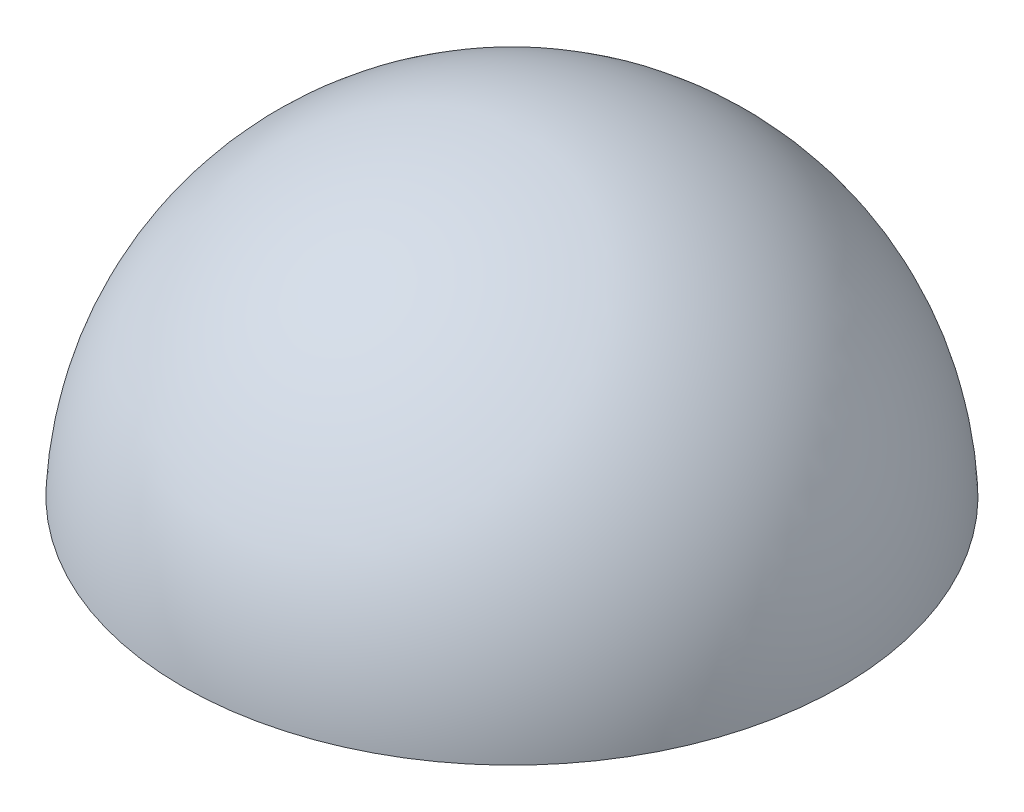
SolidWorks part; units mm, degrees
ref_plane "Front Plane" through (0, 0, 0) normal (0, 0, 1) x (1, 0, 0)
ref_plane "Top Plane" through (0, 0, 0) normal (0, 1, 0) x (1, 0, 0)
ref_plane "Right Plane" through (0, 0, 0) normal (1, 0, 0) x (0, 0, -1)
sketch "Sketch1" plane through (0, 0, 0) normal (0, 1, 0) x (1, 0, 0)
  line L0 (0, -44.45) -> (0, 44.45)
  arc A0 (0, 44.45) -> (0, -44.45) centre (0, 0) ccw
  arc A1 (0, 42.45) -> (0, -42.45) centre (0, 0) ccw
  circle A3 centre (0, 0) radius 44.45 construction
  circle A4 centre (0, 0) radius 42.45 construction
  point P1 (42.45, 0)
  point P6 (42.5077, 12.9959)
  dimension "D1" = 88.9
  dimension "D2" = 2
revolve "Revolve1" add sketch "Sketch1" angle 180 about L0 region at (-43.4561, 0, 0)
sketch "Sketch2" plane through (0, 0, 0) normal (0, 1, 0) x (1, 0, 0)
  circle A0 centre (0, 0) radius 44.45
extrude "Cut-Extrude1" cut sketch "Sketch2" along normal blind 2
sketch "30deg" plane through (0, 0, 0) normal (1, 0, 0) x (0, 0, -1)
  line L0 (0, 0) -> (38.4948, 22.225) construction
  line L1 (0, 0) -> (44.45, 0) construction
  line L7 (0, 0) -> (22.225, 38.4948) construction
  line L8 (0, 0) -> (44.45, 0) construction
  line L10 (0, 0) -> (38.4948, 22.225) construction
  line L25 (0, 0) -> (0, 49000) construction
  dimension "D2" = 3
  dimension "D3" = 30
  dimension "D1" = 44.45
sketch "Sketch4" plane through (0, 0, 0) normal (0, 1, 0) x (1, 0, 0)
  line L0 (0, 0) -> (0, 43.45)
  line L1 (0.5, 44.45) -> (-0.5, 44.45)
  line L2 (-0.5, 43.45) -> (0.5, 43.45)
  line L3 (-0.5, 43.45) -> (-0.5, 44.45)
  line L4 (0.5, 43.45) -> (0.5, 44.45)
  line L5 (0, 0) -> (21.725, 37.6288)
  line L6 (21.292, 37.8788) -> (21.792, 38.7448)
  line L7 (21.292, 37.8788) -> (22.158, 37.3788)
  line L8 (22.158, 37.3788) -> (22.658, 38.2448)
  line L9 (22.658, 38.2448) -> (21.792, 38.7448)
  line L10 (0, 0) -> (37.6288, 21.725)
  line L11 (37.3788, 22.158) -> (38.2448, 22.658)
  line L12 (37.3788, 22.158) -> (37.8788, 21.292)
  line L13 (37.8788, 21.292) -> (38.7448, 21.792)
  line L14 (38.7448, 21.792) -> (38.2448, 22.658)
  line L15 (0, 0) -> (43.45, 0)
  line L16 (43.45, 0.5) -> (44.45, 0.5)
  line L17 (43.45, 0.5) -> (43.45, -0.5)
  line L18 (43.45, -0.5) -> (44.45, -0.5)
  line L19 (44.45, -0.5) -> (44.45, 0.5)
  line L20 (0, 0) -> (37.6288, -21.725)
  line L21 (37.8788, -21.292) -> (38.7448, -21.792)
  line L22 (37.8788, -21.292) -> (37.3788, -22.158)
  line L23 (37.3788, -22.158) -> (38.2448, -22.658)
  line L24 (38.2448, -22.658) -> (38.7448, -21.792)
  line L25 (0, 0) -> (21.725, -37.6288)
  line L26 (22.158, -37.3788) -> (22.658, -38.2448)
  line L27 (22.158, -37.3788) -> (21.292, -37.8788)
  line L28 (21.292, -37.8788) -> (21.792, -38.7448)
  line L29 (21.792, -38.7448) -> (22.658, -38.2448)
  line L30 (0, 0) -> (0, -43.45)
  line L31 (0.5, -43.45) -> (0.5, -44.45)
  line L32 (0.5, -43.45) -> (-0.5, -43.45)
  line L33 (-0.5, -43.45) -> (-0.5, -44.45)
  line L34 (-0.5, -44.45) -> (0.5, -44.45)
  line L35 (0, 0) -> (-21.725, -37.6288)
  line L36 (-21.292, -37.8788) -> (-21.792, -38.7448)
  line L37 (-21.292, -37.8788) -> (-22.158, -37.3788)
  line L38 (-22.158, -37.3788) -> (-22.658, -38.2448)
  line L39 (-22.658, -38.2448) -> (-21.792, -38.7448)
  line L40 (0, 0) -> (-37.6288, -21.725)
  line L41 (-37.3788, -22.158) -> (-38.2448, -22.658)
  line L42 (-37.3788, -22.158) -> (-37.8788, -21.292)
  line L43 (-37.8788, -21.292) -> (-38.7448, -21.792)
  line L44 (-38.7448, -21.792) -> (-38.2448, -22.658)
  line L45 (0, 0) -> (-43.45, 0)
  line L46 (-43.45, -0.5) -> (-44.45, -0.5)
  line L47 (-43.45, -0.5) -> (-43.45, 0.5)
  line L48 (-43.45, 0.5) -> (-44.45, 0.5)
  line L49 (-44.45, 0.5) -> (-44.45, -0.5)
  line L50 (0, 0) -> (-37.6288, 21.725)
  line L51 (-37.8788, 21.292) -> (-38.7448, 21.792)
  line L52 (-37.8788, 21.292) -> (-37.3788, 22.158)
  line L53 (-37.3788, 22.158) -> (-38.2448, 22.658)
  line L54 (-38.2448, 22.658) -> (-38.7448, 21.792)
  line L55 (0, 0) -> (-21.725, 37.6288)
  line L56 (-22.158, 37.3788) -> (-22.658, 38.2448)
  line L57 (-22.158, 37.3788) -> (-21.292, 37.8788)
  line L58 (-21.292, 37.8788) -> (-21.792, 38.7448)
  line L59 (-21.792, 38.7448) -> (-22.658, 38.2448)
  line L60 (0, 0) -> (0, 43.45) construction
  line L61 (0, 0) -> (21.725, 37.6288) construction
  circle A0 centre (0, 0) radius 44.45 construction
  point P7 (0, 44.45)
  point P10 (0, 43.45)
  dimension "D1" = 88.9
  dimension "D2" = 1
  dimension "D3" = 1
  dimension "D5" = 30
  dimension "D4" = 12
ref_plane "Plane1" through (0, 44.45, 0) normal (0, 1, 0) x (1, 0, 0)
sketch "Sketch5" plane through (0, 44.45, 0) normal (0, 1, 0) x (1, 0, 0)
  circle A0 centre (0, 0) radius 0.5
  dimension "D1" = 1
sketch "Sketch6" plane through (0, 0, 0) normal (0, 0, 1) x (1, 0, 0)
  line L0 (44.45, 0) -> (-44.45, 0) construction
  line L1 (-43.45, 0) -> (-44.45, 0) construction
  arc A0 (-44.45, 0) -> (0, 44.45) centre (0, 0) cw
ref_axis "Axis1" through (0, 117.8347, 0) along (0, -1, 0)
sketch "Sketch7" plane through (0, 44.45, 0) normal (0, 1, 0) x (1, 0, 0)
  line L0 (0, 0) -> (0, 88.8986) construction
  line L4 (-0.5, 38.9916) -> (-0.5, 88.8986)
  line L5 (0.5, 38.9916) -> (0.5, 88.8986)
  line L7 (-0.5, 22.7195) -> (-0.5, 37.9915)
  line L9 (0.5, 22.7195) -> (0.5, 37.9915)
  line L10 (0, 0) -> (44.4493, 76.9884) construction
  line L11 (19.0628, 34.0177) -> (44.0163, 77.2384)
  line L12 (19.9288, 33.5177) -> (44.8823, 76.7384)
  line L13 (10.9267, 19.9257) -> (18.5628, 33.1516)
  line L14 (11.7928, 19.4257) -> (19.4288, 32.6516)
  line L17 (0, 0) -> (76.9884, 44.4493) construction
  line L18 (33.5177, 19.9288) -> (76.7384, 44.8823)
  line L19 (34.0177, 19.0628) -> (77.2384, 44.0163)
  line L20 (19.4257, 11.7928) -> (32.6516, 19.4288)
  line L21 (19.9257, 10.9267) -> (33.1516, 18.5628)
  line L24 (0, 0) -> (88.8986, 0) construction
  line L25 (38.9916, 0.5) -> (88.8986, 0.5)
  line L26 (38.9916, -0.5) -> (88.8986, -0.5)
  line L27 (22.7195, 0.5) -> (37.9915, 0.5)
  line L28 (22.7195, -0.5) -> (37.9915, -0.5)
  line L31 (0, 0) -> (76.9884, -44.4493) construction
  line L32 (34.0177, -19.0628) -> (77.2384, -44.0163)
  line L33 (33.5177, -19.9288) -> (76.7384, -44.8823)
  line L34 (19.9257, -10.9267) -> (33.1516, -18.5628)
  line L35 (19.4257, -11.7928) -> (32.6516, -19.4288)
  line L38 (0, 0) -> (44.4493, -76.9884) construction
  line L39 (19.9288, -33.5177) -> (44.8823, -76.7384)
  line L40 (19.0628, -34.0177) -> (44.0163, -77.2384)
  line L41 (11.7928, -19.4257) -> (19.4288, -32.6516)
  line L42 (10.9267, -19.9257) -> (18.5628, -33.1516)
  line L45 (0, 0) -> (0, -88.8986) construction
  line L46 (0.5, -38.9916) -> (0.5, -88.8986)
  line L47 (-0.5, -38.9916) -> (-0.5, -88.8986)
  line L48 (0.5, -22.7195) -> (0.5, -37.9915)
  line L49 (-0.5, -22.7195) -> (-0.5, -37.9915)
  line L52 (0, 0) -> (-44.4493, -76.9884) construction
  line L53 (-19.0628, -34.0177) -> (-44.0163, -77.2384)
  line L54 (-19.9288, -33.5177) -> (-44.8823, -76.7384)
  line L55 (-10.9267, -19.9257) -> (-18.5628, -33.1516)
  line L56 (-11.7928, -19.4257) -> (-19.4288, -32.6516)
  line L59 (0, 0) -> (-76.9884, -44.4493) construction
  line L60 (-33.5177, -19.9288) -> (-76.7384, -44.8823)
  line L61 (-34.0177, -19.0628) -> (-77.2384, -44.0163)
  line L62 (-19.4257, -11.7928) -> (-32.6516, -19.4288)
  line L63 (-19.9257, -10.9267) -> (-33.1516, -18.5628)
  line L66 (0, 0) -> (-88.8986, 0) construction
  line L67 (-38.9916, -0.5) -> (-88.8986, -0.5)
  line L68 (-38.9916, 0.5) -> (-88.8986, 0.5)
  line L69 (-22.7195, -0.5) -> (-37.9915, -0.5)
  line L70 (-22.7195, 0.5) -> (-37.9915, 0.5)
  line L73 (0, 0) -> (-76.9884, 44.4493) construction
  line L74 (-34.0177, 19.0628) -> (-77.2384, 44.0163)
  line L75 (-33.5177, 19.9288) -> (-76.7384, 44.8823)
  line L76 (-19.9257, 10.9267) -> (-33.1516, 18.5628)
  line L77 (-19.4257, 11.7928) -> (-32.6516, 19.4288)
  line L80 (0, 0) -> (-44.4493, 76.9884) construction
  line L81 (-19.9288, 33.5177) -> (-44.8823, 76.7384)
  line L82 (-19.0628, 34.0177) -> (-44.0163, 77.2384)
  line L83 (-11.7928, 19.4257) -> (-19.4288, 32.6516)
  line L84 (-10.9267, 19.9257) -> (-18.5628, 33.1516)
  line L87 (0, 0) -> (0.5, 0) construction
  line L89 (-0.5, 1.866) -> (-0.5, 21.7192)
  line L90 (-0.5, 1.866) -> (-10.4266, 19.0594)
  line L91 (0.5, 1.866) -> (10.4266, 19.0594)
  line L92 (0.5, 1.866) -> (0.5, 21.7192)
  line L93 (1.366, 1.366) -> (18.5594, 11.2926)
  line L94 (1.366, 1.366) -> (11.2926, 18.5594)
  line L95 (1.866, 0.5) -> (21.7192, 0.5)
  line L96 (1.866, 0.5) -> (19.0594, 10.4266)
  line L97 (1.866, -0.5) -> (19.0594, -10.4266)
  line L98 (1.866, -0.5) -> (21.7192, -0.5)
  line L99 (1.366, -1.366) -> (11.2926, -18.5594)
  line L100 (1.366, -1.366) -> (18.5594, -11.2926)
  line L101 (0.5, -1.866) -> (0.5, -21.7192)
  line L102 (0.5, -1.866) -> (10.4266, -19.0594)
  line L103 (-0.5, -1.866) -> (-10.4266, -19.0594)
  line L104 (-0.5, -1.866) -> (-0.5, -21.7192)
  line L105 (-1.366, -1.366) -> (-11.2926, -18.5594)
  line L106 (-1.366, -1.366) -> (-18.5594, -11.2926)
  line L107 (-1.866, -0.5) -> (-21.7192, -0.5)
  line L108 (-1.866, -0.5) -> (-19.0594, -10.4266)
  line L109 (-1.866, 0.5) -> (-19.0594, 10.4266)
  line L110 (-1.866, 0.5) -> (-21.7192, 0.5)
  line L111 (-1.366, 1.366) -> (-11.2926, 18.5594)
  line L112 (-1.366, 1.366) -> (-18.5594, 11.2926)
  circle A0 centre (0, 0) radius 22.225 construction
  circle A1 centre (0, 0) radius 38.4948 construction
  arc A2 (-0.5, 38.9916) -> (-19.0628, 34.0177) centre (0, 0) ccw
  arc A3 (-0.5, 22.7195) -> (-10.9267, 19.9257) centre (0, 0) ccw
  arc A4 (-0.5, 37.9915) -> (-18.5628, 33.1516) centre (0, 0) ccw
  arc A5 (-0.5, 21.7192) -> (-10.4266, 19.0594) centre (0, 0) ccw
  arc A6 (0.5, 88.8986) -> (-0.5, 88.8986) centre (0, 0) ccw
  circle A9 centre (0, 0) radius 88.9 construction
  circle A10 centre (0, 0) radius 38.9948 construction
  circle A11 centre (0, 0) radius 37.9948 construction
  circle A13 centre (0, 0) radius 21.725 construction
  circle A14 centre (0, 0) radius 22.725 construction
  arc A15 (44.8823, 76.7384) -> (44.0163, 77.2384) centre (0, 0) ccw
  arc A16 (77.2384, 44.0163) -> (76.7384, 44.8823) centre (0, 0) ccw
  arc A17 (88.8986, -0.5) -> (88.8986, 0.5) centre (0, 0) ccw
  arc A18 (76.7384, -44.8823) -> (77.2384, -44.0163) centre (0, 0) ccw
  arc A19 (44.0163, -77.2384) -> (44.8823, -76.7384) centre (0, 0) ccw
  arc A20 (-0.5, -88.8986) -> (0.5, -88.8986) centre (0, 0) ccw
  arc A21 (-44.8823, -76.7384) -> (-44.0163, -77.2384) centre (0, 0) ccw
  arc A22 (-77.2384, -44.0163) -> (-76.7384, -44.8823) centre (0, 0) ccw
  arc A23 (-88.8986, 0.5) -> (-88.8986, -0.5) centre (0, 0) ccw
  arc A24 (-76.7384, 44.8823) -> (-77.2384, 44.0163) centre (0, 0) ccw
  arc A25 (-44.0163, 77.2384) -> (-44.8823, 76.7384) centre (0, 0) ccw
  arc A26 (-34.0177, 19.0628) -> (-38.9916, 0.5) centre (0, 0) ccw
  arc A27 (-33.1516, 18.5628) -> (-37.9915, 0.5) centre (0, 0) ccw
  arc A28 (-19.9288, 33.5177) -> (-33.5177, 19.9288) centre (0, 0) ccw
  arc A29 (-19.4288, 32.6516) -> (-32.6516, 19.4288) centre (0, 0) ccw
  arc A30 (19.0628, 34.0177) -> (0.5, 38.9916) centre (0, 0) ccw
  arc A31 (18.5628, 33.1516) -> (0.5, 37.9915) centre (0, 0) ccw
  arc A32 (32.6516, 19.4288) -> (19.4288, 32.6516) centre (0, 0) ccw
  arc A33 (33.5177, 19.9288) -> (19.9288, 33.5177) centre (0, 0) ccw
  arc A34 (37.9915, 0.5) -> (33.1516, 18.5628) centre (0, 0) ccw
  arc A35 (38.9916, 0.5) -> (34.0177, 19.0628) centre (0, 0) ccw
  arc A36 (33.1516, -18.5628) -> (37.9915, -0.5) centre (0, 0) ccw
  arc A37 (34.0177, -19.0628) -> (38.9916, -0.5) centre (0, 0) ccw
  arc A38 (19.4288, -32.6516) -> (32.6516, -19.4288) centre (0, 0) ccw
  arc A39 (19.9288, -33.5177) -> (33.5177, -19.9288) centre (0, 0) ccw
  arc A40 (0.5, -37.9915) -> (18.5628, -33.1516) centre (0, 0) ccw
  arc A41 (0.5, -38.9916) -> (19.0628, -34.0177) centre (0, 0) ccw
  arc A42 (-18.5628, -33.1516) -> (-0.5, -37.9915) centre (0, 0) ccw
  arc A43 (-19.0628, -34.0177) -> (-0.5, -38.9916) centre (0, 0) ccw
  arc A44 (-33.5177, -19.9288) -> (-19.9288, -33.5177) centre (0, 0) ccw
  arc A45 (-32.6516, -19.4288) -> (-19.4288, -32.6516) centre (0, 0) ccw
  arc A46 (-38.9916, -0.5) -> (-34.0177, -19.0628) centre (0, 0) ccw
  arc A47 (-37.9915, -0.5) -> (-33.1516, -18.5628) centre (0, 0) ccw
  arc A48 (-11.7928, 19.4257) -> (-19.4257, 11.7928) centre (0, 0) ccw
  arc A49 (-11.2926, 18.5594) -> (-18.5594, 11.2926) centre (0, 0) ccw
  arc A50 (-19.9257, 10.9267) -> (-22.7195, 0.5) centre (0, 0) ccw
  arc A51 (-19.0594, 10.4266) -> (-21.7192, 0.5) centre (0, 0) ccw
  arc A52 (-21.7192, -0.5) -> (-19.0594, -10.4266) centre (0, 0) ccw
  arc A53 (-22.7195, -0.5) -> (-19.9257, -10.9267) centre (0, 0) ccw
  arc A54 (10.4266, 19.0594) -> (0.5, 21.7192) centre (0, 0) ccw
  arc A55 (10.9267, 19.9257) -> (0.5, 22.7195) centre (0, 0) ccw
  arc A56 (18.5594, 11.2926) -> (11.2926, 18.5594) centre (0, 0) ccw
  arc A57 (19.4257, 11.7928) -> (11.7928, 19.4257) centre (0, 0) ccw
  arc A58 (21.7192, 0.5) -> (19.0594, 10.4266) centre (0, 0) ccw
  arc A59 (22.7195, 0.5) -> (19.9257, 10.9267) centre (0, 0) ccw
  arc A60 (19.9257, -10.9267) -> (22.7195, -0.5) centre (0, 0) ccw
  arc A61 (19.0594, -10.4266) -> (21.7192, -0.5) centre (0, 0) ccw
  arc A62 (11.2926, -18.5594) -> (18.5594, -11.2926) centre (0, 0) ccw
  arc A63 (11.7928, -19.4257) -> (19.4257, -11.7928) centre (0, 0) ccw
  arc A64 (0.5, -22.7195) -> (10.9267, -19.9257) centre (0, 0) ccw
  arc A65 (0.5, -21.7192) -> (10.4266, -19.0594) centre (0, 0) ccw
  arc A66 (-10.4266, -19.0594) -> (-0.5, -21.7192) centre (0, 0) ccw
  arc A67 (-10.9267, -19.9257) -> (-0.5, -22.7195) centre (0, 0) ccw
  arc A68 (-19.4257, -11.7928) -> (-11.7928, -19.4257) centre (0, 0) ccw
  arc A69 (-18.5594, -11.2926) -> (-11.2926, -18.5594) centre (0, 0) ccw
  point P11 (21.725, 0)
  point P13 (22.725, 0)
  point P17 (0.5, 0)
  point P19 (-0.5, 0)
  point P27 (38.9948, 0)
  point P30 (37.9948, 0)
  point P114 (-1.366, 1.366)
  dimension "D5" = 177.8
  dimension "D1" = 0.5
  dimension "D2" = 0.5
  dimension "D6" = 12
sketch "Sketch9" plane through (0, 44.45, 0) normal (0, 1, 0) x (1, 0, 0)
  line L0 (0, 0) -> (0, -88.9)
  circle A0 centre (0, 0) radius 22.225
  circle A1 centre (0, 0) radius 38.4948
  circle A2 centre (0, 0) radius 88.9
  circle A3 centre (0, 0) radius 38.4948 construction
  circle A4 centre (0, 0) radius 22.225 construction
  dimension "D1" = 177.8
sketch "Sketch10" plane through (0, 44.45, 0) normal (0, 1, 0) x (1, 0, 0)
  line L0 (88.9, 0) -> (-88.9, 0) construction
  line L1 (0, 88.9) -> (0, -88.9) construction
  line L2 (-29.64, 88.9) -> (-29.64, -88.9) construction
  line L3 (-59.28, 88.9) -> (-59.28, -88.9) construction
  line L4 (-88.92, 88.9) -> (-88.92, -88.9) construction
  line L5 (29.64, 88.9) -> (29.64, -88.9) construction
  line L6 (59.28, 88.9) -> (59.28, -88.9) construction
  line L7 (88.92, 88.9) -> (88.92, -88.9) construction
  line L8 (-89.42, 88.9) -> (-89.42, -88.9)
  line L9 (-59.78, 88.9) -> (-59.78, 0.5)
  line L10 (-30.14, 88.9) -> (-30.14, 0.5)
  line L11 (-0.5, 88.9) -> (-0.5, 0.5)
  line L12 (29.14, 88.9) -> (29.14, 0.5)
  line L13 (58.78, 88.9) -> (58.78, 0.5)
  line L14 (88.42, 88.9) -> (88.42, 0.5)
  line L15 (-88.42, 88.9) -> (-88.42, 0.5)
  line L16 (-58.78, 88.9) -> (-58.78, 0.5)
  line L17 (-29.14, 88.9) -> (-29.14, 0.5)
  line L18 (0.5, 88.9) -> (0.5, 0.5)
  line L19 (30.14, 88.9) -> (30.14, 0.5)
  line L20 (59.78, 88.9) -> (59.78, 0.5)
  line L21 (89.42, 88.9) -> (89.42, -88.9)
  line L22 (88.42, 0.5) -> (59.78, 0.5)
  line L23 (88.42, -0.5) -> (59.78, -0.5)
  line L24 (-88.42, -0.5) -> (-88.42, -88.9)
  line L25 (88.9, 0.5) -> (-88.9, 0.5) construction
  line L26 (88.9, -0.5) -> (-88.9, -0.5) construction
  line L27 (-59.78, 0.5) -> (-88.42, 0.5)
  line L28 (-88.42, 88.9) -> (-88.42, -88.9) construction
  line L29 (-59.78, -0.5) -> (-88.42, -0.5)
  line L30 (-59.78, -0.5) -> (-59.78, -88.9)
  line L31 (-58.78, -0.5) -> (-58.78, -88.9)
  line L32 (-59.78, 88.9) -> (-59.78, -88.9) construction
  line L33 (-30.14, -0.5) -> (-30.14, -88.9)
  line L34 (-58.78, 88.9) -> (-58.78, -88.9) construction
  line L35 (-30.14, 88.9) -> (-30.14, -88.9) construction
  line L36 (-29.14, -0.5) -> (-29.14, -88.9)
  line L37 (-29.14, 88.9) -> (-29.14, -88.9) construction
  line L38 (-0.5, -0.5) -> (-0.5, -88.9)
  line L39 (-0.5, 88.9) -> (-0.5, -88.9) construction
  line L40 (0.5, -0.5) -> (0.5, -88.9)
  line L41 (0.5, 88.9) -> (0.5, -88.9) construction
  line L42 (29.14, -0.5) -> (29.14, -88.9)
  line L43 (29.14, 88.9) -> (29.14, -88.9) construction
  line L44 (30.14, -0.5) -> (30.14, -88.9)
  line L45 (30.14, 88.9) -> (30.14, -88.9) construction
  line L46 (58.78, -0.5) -> (58.78, -88.9)
  line L47 (58.78, 88.9) -> (58.78, -88.9) construction
  line L48 (59.78, -0.5) -> (59.78, -88.9)
  line L49 (59.78, 88.9) -> (59.78, -88.9) construction
  line L50 (88.42, -0.5) -> (88.42, -88.9)
  line L51 (88.42, 88.9) -> (88.42, -88.9) construction
  line L52 (58.78, 0.5) -> (30.14, 0.5)
  line L53 (58.78, -0.5) -> (30.14, -0.5)
  line L54 (-30.14, 0.5) -> (-58.78, 0.5)
  line L55 (-30.14, -0.5) -> (-58.78, -0.5)
  line L56 (-0.5, 0.5) -> (-29.14, 0.5)
  line L57 (-0.5, -0.5) -> (-29.14, -0.5)
  line L58 (29.14, 0.5) -> (0.5, 0.5)
  line L59 (29.14, -0.5) -> (0.5, -0.5)
  arc A0 (-89.42, 88.9) -> (-88.42, 88.9) centre (-88.92, 88.9) cw
  arc A1 (-89.42, -88.9) -> (-88.42, -88.9) centre (-88.92, -88.9) ccw
  arc A2 (-59.78, 88.9) -> (-58.78, 88.9) centre (-59.28, 88.9) cw
  arc A3 (-59.78, -88.9) -> (-58.78, -88.9) centre (-59.28, -88.9) ccw
  arc A4 (-30.14, 88.9) -> (-29.14, 88.9) centre (-29.64, 88.9) cw
  arc A5 (-30.14, -88.9) -> (-29.14, -88.9) centre (-29.64, -88.9) ccw
  arc A6 (-0.5, 88.9) -> (0.5, 88.9) centre (0, 88.9) cw
  arc A7 (-0.5, -88.9) -> (0.5, -88.9) centre (0, -88.9) ccw
  arc A8 (29.14, 88.9) -> (30.14, 88.9) centre (29.64, 88.9) cw
  arc A9 (29.14, -88.9) -> (30.14, -88.9) centre (29.64, -88.9) ccw
  arc A10 (58.78, 88.9) -> (59.78, 88.9) centre (59.28, 88.9) cw
  arc A11 (58.78, -88.9) -> (59.78, -88.9) centre (59.28, -88.9) ccw
  arc A12 (88.42, 88.9) -> (89.42, 88.9) centre (88.92, 88.9) cw
  arc A13 (88.42, -88.9) -> (89.42, -88.9) centre (88.92, -88.9) ccw
  arc A15 (-88.9, 0.5) -> (-88.92, 0.4996) centre (-88.9, 0) ccw
  arc A16 (-88.92, -0.4996) -> (-88.9, -0.5) centre (-88.9, 0) ccw
  point P4 (0, 0)
  point P8 (0, 0)
  dimension "D1" = 177.8
  dimension "D3" = 0.5
  dimension "D4" = 0.5
  dimension "D5" = 0.5
  dimension "D6" = 0.5
  dimension "D2" = 4
sketch "Sketch13" plane through (0, 44.45, 0) normal (0, 1, 0) x (1, 0, 0)
  line L0 (0, -11.5265) -> (0, 11.5265) construction
  line L1 (-11.5265, 0) -> (11.5265, 0) construction
  line L2 (-11.5265, -0.5) -> (-0.5, -0.5)
  line L3 (-18.1069, 3.2902) -> (-11.5265, 3.2902) construction
  line L4 (-18.1069, 3.2902) -> (-18.1069, -3.2902) construction
  line L5 (-18.1069, -3.2902) -> (-11.5265, -3.2902) construction
  line L6 (-11.5265, 3.2902) -> (-11.5265, -3.2902) construction
  line L7 (-3.2902, 18.1069) -> (3.2902, 18.1069) construction
  line L8 (-3.2902, 18.1069) -> (-3.2902, 11.5265) construction
  line L9 (-3.2902, 11.5265) -> (3.2902, 11.5265) construction
  line L10 (3.2902, 18.1069) -> (3.2902, 11.5265) construction
  line L11 (0.5, -11.5265) -> (0.5, -0.5)
  line L12 (-11.5265, 0.5) -> (-0.5, 0.5)
  line L13 (-0.5, -11.5265) -> (-0.5, -0.5)
  line L14 (-0.5, 0.5) -> (-0.5, 11.5265)
  line L15 (0.5, 0.5) -> (0.5, 11.5265)
  line L16 (-0.5, -11.5265) -> (-0.5, 11.5265) construction
  line L17 (0.5, 0.5) -> (11.5265, 0.5)
  line L18 (0.5, -11.5265) -> (0.5, 11.5265) construction
  line L19 (0.5, -0.5) -> (11.5265, -0.5)
  line L20 (-11.5265, 0.5) -> (11.5265, 0.5) construction
  line L21 (-11.5265, 0.5) -> (-11.5265, -0.5)
  line L22 (-11.5265, -0.5) -> (11.5265, -0.5) construction
  line L23 (11.5265, 0.5) -> (11.5265, -0.5)
  line L24 (-0.5, -11.5265) -> (0.5, -11.5265)
  line L25 (-0.5, 11.5265) -> (0.5, 11.5265)
  line L26 (18.1035, -0.5) -> (29.13, -0.5)
  line L27 (30.13, -11.5265) -> (30.13, -0.5)
  line L28 (18.1035, 0.5) -> (29.13, 0.5)
  line L29 (29.13, -11.5265) -> (29.13, -0.5)
  line L30 (29.13, 0.5) -> (29.13, 11.5265)
  line L31 (30.13, 0.5) -> (30.13, 11.5265)
  line L32 (30.13, 0.5) -> (41.1565, 0.5)
  line L33 (30.13, -0.5) -> (41.1565, -0.5)
  line L34 (18.1035, 0.5) -> (18.1035, -0.5)
  line L35 (41.1565, 0.5) -> (41.1565, -0.5)
  line L36 (29.13, -11.5265) -> (30.13, -11.5265)
  line L37 (29.13, 11.5265) -> (30.13, 11.5265)
  line L38 (29.63, -11.5265) -> (29.63, 11.5265) construction
  line L39 (18.1035, 0) -> (41.1565, 0) construction
  line L40 (11.5231, 3.2902) -> (18.1035, 3.2902) construction
  line L41 (11.5231, 3.2902) -> (11.5231, -3.2902) construction
  line L42 (11.5231, -3.2902) -> (18.1035, -3.2902) construction
  line L43 (18.1035, 3.2902) -> (18.1035, -3.2902) construction
  line L44 (26.3398, 18.1069) -> (32.9202, 18.1069) construction
  line L45 (26.3398, 18.1069) -> (26.3398, 11.5265) construction
  line L46 (26.3398, 11.5265) -> (32.9202, 11.5265) construction
  line L47 (32.9202, 18.1069) -> (32.9202, 11.5265) construction
  line L48 (47.7335, -0.5) -> (58.76, -0.5)
  line L49 (59.76, -11.5265) -> (59.76, -0.5)
  line L50 (47.7335, 0.5) -> (58.76, 0.5)
  line L51 (58.76, -11.5265) -> (58.76, -0.5)
  line L52 (58.76, 0.5) -> (58.76, 11.5265)
  line L53 (59.76, 0.5) -> (59.76, 11.5265)
  line L54 (59.76, 0.5) -> (70.7865, 0.5)
  line L55 (59.76, -0.5) -> (70.7865, -0.5)
  line L56 (47.7335, 0.5) -> (47.7335, -0.5)
  line L57 (70.7865, 0.5) -> (70.7865, -0.5)
  line L58 (58.76, -11.5265) -> (59.76, -11.5265)
  line L59 (58.76, 11.5265) -> (59.76, 11.5265)
  line L60 (59.26, -11.5265) -> (59.26, 11.5265) construction
  line L61 (47.7335, 0) -> (70.7865, 0) construction
  line L62 (41.1531, 3.2902) -> (47.7335, 3.2902) construction
  line L63 (41.1531, 3.2902) -> (41.1531, -3.2902) construction
  line L64 (41.1531, -3.2902) -> (47.7335, -3.2902) construction
  line L65 (47.7335, 3.2902) -> (47.7335, -3.2902) construction
  line L66 (55.9698, 18.1069) -> (62.5502, 18.1069) construction
  line L67 (55.9698, 18.1069) -> (55.9698, 11.5265) construction
  line L68 (55.9698, 11.5265) -> (62.5502, 11.5265) construction
  line L69 (62.5502, 18.1069) -> (62.5502, 11.5265) construction
  line L70 (-11.5265, 29.13) -> (-0.5, 29.13)
  line L71 (0.5, 18.1035) -> (0.5, 29.13)
  line L72 (-11.5265, 30.13) -> (-0.5, 30.13)
  line L73 (-0.5, 18.1035) -> (-0.5, 29.13)
  line L74 (-0.5, 30.13) -> (-0.5, 41.1565)
  line L75 (0.5, 30.13) -> (0.5, 41.1565)
  line L76 (0.5, 30.13) -> (11.5265, 30.13)
  line L77 (0.5, 29.13) -> (11.5265, 29.13)
  line L78 (-11.5265, 30.13) -> (-11.5265, 29.13)
  line L79 (11.5265, 30.13) -> (11.5265, 29.13)
  line L80 (-0.5, 18.1035) -> (0.5, 18.1035)
  line L81 (-0.5, 41.1565) -> (0.5, 41.1565)
  line L82 (18.1035, 29.13) -> (29.13, 29.13)
  line L83 (30.13, 18.1035) -> (30.13, 29.13)
  line L84 (18.1035, 30.13) -> (29.13, 30.13)
  line L85 (29.13, 18.1035) -> (29.13, 29.13)
  line L86 (29.13, 30.13) -> (29.13, 41.1565)
  line L87 (30.13, 30.13) -> (30.13, 41.1565)
  line L88 (30.13, 30.13) -> (41.1565, 30.13)
  line L89 (30.13, 29.13) -> (41.1565, 29.13)
  line L90 (18.1035, 30.13) -> (18.1035, 29.13)
  line L91 (41.1565, 30.13) -> (41.1565, 29.13)
  line L92 (29.13, 18.1035) -> (30.13, 18.1035)
  line L93 (29.13, 41.1565) -> (30.13, 41.1565)
  line L94 (47.7335, 29.13) -> (58.76, 29.13)
  line L95 (59.76, 18.1035) -> (59.76, 29.13)
  line L96 (47.7335, 30.13) -> (58.76, 30.13)
  line L97 (58.76, 18.1035) -> (58.76, 29.13)
  line L98 (58.76, 30.13) -> (58.76, 41.1565)
  line L99 (59.76, 30.13) -> (59.76, 41.1565)
  line L100 (59.76, 30.13) -> (70.7865, 30.13)
  line L101 (59.76, 29.13) -> (70.7865, 29.13)
  line L102 (47.7335, 30.13) -> (47.7335, 29.13)
  line L103 (70.7865, 30.13) -> (70.7865, 29.13)
  line L104 (58.76, 18.1035) -> (59.76, 18.1035)
  line L105 (58.76, 41.1565) -> (59.76, 41.1565)
  line L106 (0, 18.1035) -> (0, 41.1565) construction
  line L107 (-11.5265, 29.63) -> (11.5265, 29.63) construction
  line L108 (-18.1069, 32.9202) -> (-11.5265, 32.9202) construction
  line L109 (-18.1069, 32.9202) -> (-18.1069, 26.3398) construction
  line L110 (-18.1069, 26.3398) -> (-11.5265, 26.3398) construction
  line L111 (-11.5265, 32.9202) -> (-11.5265, 26.3398) construction
  line L112 (-3.2902, 47.7369) -> (3.2902, 47.7369) construction
  line L113 (-3.2902, 47.7369) -> (-3.2902, 41.1565) construction
  line L114 (-3.2902, 41.1565) -> (3.2902, 41.1565) construction
  line L115 (3.2902, 47.7369) -> (3.2902, 41.1565) construction
  line L116 (29.63, 18.1035) -> (29.63, 41.1565) construction
  line L117 (18.1035, 29.63) -> (41.1565, 29.63) construction
  line L118 (11.5231, 32.9202) -> (18.1035, 32.9202) construction
  line L119 (11.5231, 32.9202) -> (11.5231, 26.3398) construction
  line L120 (11.5231, 26.3398) -> (18.1035, 26.3398) construction
  line L121 (18.1035, 32.9202) -> (18.1035, 26.3398) construction
  line L122 (26.3398, 47.7369) -> (32.9202, 47.7369) construction
  line L123 (26.3398, 47.7369) -> (26.3398, 41.1565) construction
  line L124 (26.3398, 41.1565) -> (32.9202, 41.1565) construction
  line L125 (32.9202, 47.7369) -> (32.9202, 41.1565) construction
  line L126 (59.26, 18.1035) -> (59.26, 41.1565) construction
  line L127 (47.7335, 29.63) -> (70.7865, 29.63) construction
  line L128 (41.1531, 32.9202) -> (47.7335, 32.9202) construction
  line L129 (41.1531, 32.9202) -> (41.1531, 26.3398) construction
  line L130 (41.1531, 26.3398) -> (47.7335, 26.3398) construction
  line L131 (47.7335, 32.9202) -> (47.7335, 26.3398) construction
  line L132 (55.9698, 47.7369) -> (62.5502, 47.7369) construction
  line L133 (55.9698, 47.7369) -> (55.9698, 41.1565) construction
  line L134 (55.9698, 41.1565) -> (62.5502, 41.1565) construction
  line L135 (62.5502, 47.7369) -> (62.5502, 41.1565) construction
  line L136 (-11.5265, 58.76) -> (-0.5, 58.76)
  line L137 (0.5, 47.7335) -> (0.5, 58.76)
  line L138 (-11.5265, 59.76) -> (-0.5, 59.76)
  line L139 (-0.5, 47.7335) -> (-0.5, 58.76)
  line L140 (-0.5, 59.76) -> (-0.5, 70.7865)
  line L141 (0.5, 59.76) -> (0.5, 70.7865)
  line L142 (0.5, 59.76) -> (11.5265, 59.76)
  line L143 (0.5, 58.76) -> (11.5265, 58.76)
  line L144 (-11.5265, 59.76) -> (-11.5265, 58.76)
  line L145 (11.5265, 59.76) -> (11.5265, 58.76)
  line L146 (-0.5, 47.7335) -> (0.5, 47.7335)
  line L147 (-0.5, 70.7865) -> (0.5, 70.7865)
  line L148 (18.1035, 58.76) -> (29.13, 58.76)
  line L149 (30.13, 47.7335) -> (30.13, 58.76)
  line L150 (18.1035, 59.76) -> (29.13, 59.76)
  line L151 (29.13, 47.7335) -> (29.13, 58.76)
  line L152 (29.13, 59.76) -> (29.13, 70.7865)
  line L153 (30.13, 59.76) -> (30.13, 70.7865)
  line L154 (30.13, 59.76) -> (41.1565, 59.76)
  line L155 (30.13, 58.76) -> (41.1565, 58.76)
  line L156 (18.1035, 59.76) -> (18.1035, 58.76)
  line L157 (41.1565, 59.76) -> (41.1565, 58.76)
  line L158 (29.13, 47.7335) -> (30.13, 47.7335)
  line L159 (29.13, 70.7865) -> (30.13, 70.7865)
  line L160 (47.7335, 58.76) -> (58.76, 58.76)
  line L161 (59.76, 47.7335) -> (59.76, 58.76)
  line L162 (47.7335, 59.76) -> (58.76, 59.76)
  line L163 (58.76, 47.7335) -> (58.76, 58.76)
  line L164 (58.76, 59.76) -> (58.76, 70.7865)
  line L165 (59.76, 59.76) -> (59.76, 70.7865)
  line L166 (59.76, 59.76) -> (70.7865, 59.76)
  line L167 (59.76, 58.76) -> (70.7865, 58.76)
  line L168 (47.7335, 59.76) -> (47.7335, 58.76)
  line L169 (70.7865, 59.76) -> (70.7865, 58.76)
  line L170 (58.76, 47.7335) -> (59.76, 47.7335)
  line L171 (58.76, 70.7865) -> (59.76, 70.7865)
  line L172 (0, 47.7335) -> (0, 70.7865) construction
  line L173 (-11.5265, 59.26) -> (11.5265, 59.26) construction
  line L174 (-18.1069, 62.5502) -> (-11.5265, 62.5502) construction
  line L175 (-18.1069, 62.5502) -> (-18.1069, 55.9698) construction
  line L176 (-18.1069, 55.9698) -> (-11.5265, 55.9698) construction
  line L177 (-11.5265, 62.5502) -> (-11.5265, 55.9698) construction
  line L178 (-3.2902, 77.3669) -> (3.2902, 77.3669) construction
  line L179 (-3.2902, 77.3669) -> (-3.2902, 70.7865) construction
  line L180 (-3.2902, 70.7865) -> (3.2902, 70.7865) construction
  line L181 (3.2902, 77.3669) -> (3.2902, 70.7865) construction
  line L182 (29.63, 47.7335) -> (29.63, 70.7865) construction
  line L183 (18.1035, 59.26) -> (41.1565, 59.26) construction
  line L184 (11.5231, 62.5502) -> (18.1035, 62.5502) construction
  line L185 (11.5231, 62.5502) -> (11.5231, 55.9698) construction
  line L186 (11.5231, 55.9698) -> (18.1035, 55.9698) construction
  line L187 (18.1035, 62.5502) -> (18.1035, 55.9698) construction
  line L188 (26.3398, 77.3669) -> (32.9202, 77.3669) construction
  line L189 (26.3398, 77.3669) -> (26.3398, 70.7865) construction
  line L190 (26.3398, 70.7865) -> (32.9202, 70.7865) construction
  line L191 (32.9202, 77.3669) -> (32.9202, 70.7865) construction
  line L192 (59.26, 47.7335) -> (59.26, 70.7865) construction
  line L193 (47.7335, 59.26) -> (70.7865, 59.26) construction
  line L194 (41.1531, 62.5502) -> (47.7335, 62.5502) construction
  line L195 (41.1531, 62.5502) -> (41.1531, 55.9698) construction
  line L196 (41.1531, 55.9698) -> (47.7335, 55.9698) construction
  line L197 (47.7335, 62.5502) -> (47.7335, 55.9698) construction
  line L198 (55.9698, 77.3669) -> (62.5502, 77.3669) construction
  line L199 (55.9698, 77.3669) -> (55.9698, 70.7865) construction
  line L200 (55.9698, 70.7865) -> (62.5502, 70.7865) construction
  line L201 (62.5502, 77.3669) -> (62.5502, 70.7865) construction
  circle A0 centre (0, 0) radius 88.9 construction
  point P4 (0, 0)
  point P8 (0, 0)
  point P12 (-11.5265, 0)
  point P35 (29.63, 0)
  point P38 (29.63, 0)
  point P61 (59.26, 0)
  point P64 (59.26, 0)
  point P86 (0, 29.63)
  point P89 (0, 29.63)
  point P112 (29.63, 29.63)
  point P115 (29.63, 29.63)
  point P138 (59.26, 29.63)
  point P141 (59.26, 29.63)
  point P164 (0, 59.26)
  point P167 (0, 59.26)
  point P190 (29.63, 59.26)
  point P193 (29.63, 59.26)
  point P216 (59.26, 59.26)
  point P219 (59.26, 59.26)
  dimension "D1" = 177.8
  dimension "D2" = 29.6333
  dimension "D3" = 0.5
  dimension "D4" = 0.5
  dimension "D5" = 3
  dimension "D6" = 3
sketch "Sketch14" plane through (0, 44.45, 0) normal (0, 1, 0) x (1, 0, 0)
  line L0 (0, -77.685) -> (0, -100.155) construction
  line L13 (11.235, -88.92) -> (-11.235, -88.92) construction
  line L14 (11.235, -88.42) -> (0.5, -88.42)
  line L15 (-18.3984, -90.6291) -> (-11.235, -90.6291) construction
  line L16 (-18.3984, -90.6291) -> (-18.3984, -87.2109) construction
  line L17 (-18.3984, -87.2109) -> (-11.235, -87.2109) construction
  line L18 (-11.235, -90.6291) -> (-11.235, -87.2109) construction
  line L19 (11.235, -58.78) -> (0.5, -58.78)
  line L20 (-0.5, -48.045) -> (-0.5, -58.78)
  line L21 (-3.5817, -74.2288) -> (3.5817, -74.2288) construction
  line L22 (-3.5817, -74.2288) -> (-3.5817, -76.5216) construction
  line L23 (-3.5817, -76.5216) -> (3.5817, -76.5216) construction
  line L24 (3.5817, -74.2288) -> (3.5817, -76.5216) construction
  line L25 (11.235, -59.78) -> (0.5, -59.78)
  line L26 (0.5, -48.045) -> (0.5, -58.78)
  line L27 (-0.5, -77.685) -> (-0.5, -88.42)
  line L28 (11.235, -89.42) -> (0.5, -89.42)
  line L29 (0.5, -77.685) -> (0.5, -88.42)
  line L30 (11.235, -88.42) -> (11.235, -89.42)
  line L31 (-11.235, -88.42) -> (-11.235, -89.42)
  line L32 (-0.5, -77.685) -> (0.5, -77.685)
  line L33 (-0.5, -100.155) -> (0.5, -100.155)
  line L34 (-0.5, -89.42) -> (-0.5, -100.155)
  line L35 (-0.5, -89.42) -> (-11.235, -89.42)
  line L36 (-0.5, -77.685) -> (-0.5, -100.155) construction
  line L37 (0.5, -89.42) -> (0.5, -100.155)
  line L38 (11.235, -89.42) -> (-11.235, -89.42) construction
  line L39 (-0.5, -88.42) -> (-11.235, -88.42)
  line L40 (0.5, -77.685) -> (0.5, -100.155) construction
  line L41 (11.235, -58.78) -> (11.235, -59.78)
  line L42 (11.235, -88.42) -> (-11.235, -88.42) construction
  line L43 (-11.235, -58.78) -> (-11.235, -59.78)
  line L44 (-0.5, -48.045) -> (0.5, -48.045)
  line L45 (-0.5, -70.515) -> (0.5, -70.515)
  line L46 (-0.5, -59.78) -> (-0.5, -70.515)
  line L47 (-0.5, -59.78) -> (-11.235, -59.78)
  line L48 (0.5, -59.78) -> (0.5, -70.515)
  line L49 (-0.5, -58.78) -> (-11.235, -58.78)
  line L50 (0, -48.045) -> (0, -70.515) construction
  line L51 (11.235, -59.28) -> (-11.235, -59.28) construction
  line L52 (-18.3984, -60.9891) -> (-11.235, -60.9891) construction
  line L53 (-18.3984, -60.9891) -> (-18.3984, -57.5709) construction
  line L54 (-18.3984, -57.5709) -> (-11.235, -57.5709) construction
  line L55 (-11.235, -60.9891) -> (-11.235, -57.5709) construction
  line L56 (-3.5817, -44.5888) -> (3.5817, -44.5888) construction
  line L57 (-3.5817, -44.5888) -> (-3.5817, -46.8816) construction
  line L58 (-3.5817, -46.8816) -> (3.5817, -46.8816) construction
  line L59 (3.5817, -44.5888) -> (3.5817, -46.8816) construction
  line L60 (11.235, -29.14) -> (0.5, -29.14)
  line L61 (-0.5, -18.405) -> (-0.5, -29.14)
  line L62 (11.235, -30.14) -> (0.5, -30.14)
  line L63 (0.5, -18.405) -> (0.5, -29.14)
  line L64 (11.235, -29.14) -> (11.235, -30.14)
  line L65 (-11.235, -29.14) -> (-11.235, -30.14)
  line L66 (-0.5, -18.405) -> (0.5, -18.405)
  line L67 (-0.5, -40.875) -> (0.5, -40.875)
  line L68 (-0.5, -30.14) -> (-0.5, -40.875)
  line L69 (-0.5, -30.14) -> (-11.235, -30.14)
  line L70 (0.5, -30.14) -> (0.5, -40.875)
  line L71 (-0.5, -29.14) -> (-11.235, -29.14)
  line L72 (0, -18.405) -> (0, -40.875) construction
  line L73 (11.235, -29.64) -> (-11.235, -29.64) construction
  line L74 (-18.3984, -31.3491) -> (-11.235, -31.3491) construction
  line L75 (-18.3984, -31.3491) -> (-18.3984, -27.9309) construction
  line L76 (-18.3984, -27.9309) -> (-11.235, -27.9309) construction
  line L77 (-11.235, -31.3491) -> (-11.235, -27.9309) construction
  line L78 (-3.5817, -14.9488) -> (3.5817, -14.9488) construction
  line L79 (-3.5817, -14.9488) -> (-3.5817, -17.2416) construction
  line L80 (-3.5817, -17.2416) -> (3.5817, -17.2416) construction
  line L81 (3.5817, -14.9488) -> (3.5817, -17.2416) construction
  line L82 (11.235, 0.5) -> (0.5, 0.5)
  line L83 (-0.5, 11.235) -> (-0.5, 0.5)
  line L84 (11.235, -0.5) -> (0.5, -0.5)
  line L85 (0.5, 11.235) -> (0.5, 0.5)
  line L86 (11.235, 0.5) -> (11.235, -0.5)
  line L87 (-11.235, 0.5) -> (-11.235, -0.5)
  line L88 (-0.5, 11.235) -> (0.5, 11.235)
  line L89 (-0.5, -11.235) -> (0.5, -11.235)
  line L90 (-0.5, -0.5) -> (-0.5, -11.235)
  line L91 (-0.5, -0.5) -> (-11.235, -0.5)
  line L92 (0.5, -0.5) -> (0.5, -11.235)
  line L93 (-0.5, 0.5) -> (-11.235, 0.5)
  line L94 (0, 11.235) -> (0, -11.235) construction
  line L95 (11.235, 0) -> (-11.235, 0) construction
  line L96 (-18.3984, -1.7091) -> (-11.235, -1.7091) construction
  line L97 (-18.3984, -1.7091) -> (-18.3984, 1.7091) construction
  line L98 (-18.3984, 1.7091) -> (-11.235, 1.7091) construction
  line L99 (-11.235, -1.7091) -> (-11.235, 1.7091) construction
  line L100 (-3.5817, 14.6912) -> (3.5817, 14.6912) construction
  line L101 (-3.5817, 14.6912) -> (-3.5817, 12.3984) construction
  line L102 (-3.5817, 12.3984) -> (3.5817, 12.3984) construction
  line L103 (3.5817, 14.6912) -> (3.5817, 12.3984) construction
  line L104 (11.235, 30.14) -> (0.5, 30.14)
  line L105 (-0.5, 40.875) -> (-0.5, 30.14)
  line L106 (11.235, 29.14) -> (0.5, 29.14)
  line L107 (0.5, 40.875) -> (0.5, 30.14)
  line L108 (11.235, 30.14) -> (11.235, 29.14)
  line L109 (-11.235, 30.14) -> (-11.235, 29.14)
  line L110 (-0.5, 40.875) -> (0.5, 40.875)
  line L111 (-0.5, 18.405) -> (0.5, 18.405)
  line L112 (-0.5, 29.14) -> (-0.5, 18.405)
  line L113 (-0.5, 29.14) -> (-11.235, 29.14)
  line L114 (0.5, 29.14) -> (0.5, 18.405)
  line L115 (-0.5, 30.14) -> (-11.235, 30.14)
  line L116 (0, 40.875) -> (0, 18.405) construction
  line L117 (11.235, 29.64) -> (-11.235, 29.64) construction
  line L118 (-18.3984, 27.9309) -> (-11.235, 27.9309) construction
  line L119 (-18.3984, 27.9309) -> (-18.3984, 31.3491) construction
  line L120 (-18.3984, 31.3491) -> (-11.235, 31.3491) construction
  line L121 (-11.235, 27.9309) -> (-11.235, 31.3491) construction
  line L122 (-3.5817, 44.3312) -> (3.5817, 44.3312) construction
  line L123 (-3.5817, 44.3312) -> (-3.5817, 42.0384) construction
  line L124 (-3.5817, 42.0384) -> (3.5817, 42.0384) construction
  line L125 (3.5817, 44.3312) -> (3.5817, 42.0384) construction
  line L126 (11.235, 59.78) -> (0.5, 59.78)
  line L127 (-0.5, 70.515) -> (-0.5, 59.78)
  line L128 (11.235, 58.78) -> (0.5, 58.78)
  line L129 (0.5, 70.515) -> (0.5, 59.78)
  line L130 (11.235, 59.78) -> (11.235, 58.78)
  line L131 (-11.235, 59.78) -> (-11.235, 58.78)
  line L132 (-0.5, 70.515) -> (0.5, 70.515)
  line L133 (-0.5, 48.045) -> (0.5, 48.045)
  line L134 (-0.5, 58.78) -> (-0.5, 48.045)
  line L135 (-0.5, 58.78) -> (-11.235, 58.78)
  line L136 (0.5, 58.78) -> (0.5, 48.045)
  line L137 (-0.5, 59.78) -> (-11.235, 59.78)
  line L138 (0, 70.515) -> (0, 48.045) construction
  line L139 (11.235, 59.28) -> (-11.235, 59.28) construction
  line L140 (-18.3984, 57.5709) -> (-11.235, 57.5709) construction
  line L141 (-18.3984, 57.5709) -> (-18.3984, 60.9891) construction
  line L142 (-18.3984, 60.9891) -> (-11.235, 60.9891) construction
  line L143 (-11.235, 57.5709) -> (-11.235, 60.9891) construction
  line L144 (-3.5817, 73.9712) -> (3.5817, 73.9712) construction
  line L145 (-3.5817, 73.9712) -> (-3.5817, 71.6784) construction
  line L146 (-3.5817, 71.6784) -> (3.5817, 71.6784) construction
  line L147 (3.5817, 73.9712) -> (3.5817, 71.6784) construction
  line L148 (11.235, 89.42) -> (0.5, 89.42)
  line L149 (-0.5, 100.155) -> (-0.5, 89.42)
  line L150 (11.235, 88.42) -> (0.5, 88.42)
  line L151 (0.5, 100.155) -> (0.5, 89.42)
  line L152 (11.235, 89.42) -> (11.235, 88.42)
  line L153 (-11.235, 89.42) -> (-11.235, 88.42)
  line L154 (-0.5, 100.155) -> (0.5, 100.155)
  line L155 (-0.5, 77.685) -> (0.5, 77.685)
  line L156 (-0.5, 88.42) -> (-0.5, 77.685)
  line L157 (-0.5, 88.42) -> (-11.235, 88.42)
  line L158 (0.5, 88.42) -> (0.5, 77.685)
  line L159 (-0.5, 89.42) -> (-11.235, 89.42)
  line L160 (0, 100.155) -> (0, 77.685) construction
  line L161 (11.235, 88.92) -> (-11.235, 88.92) construction
  line L162 (-18.3984, 87.2109) -> (-11.235, 87.2109) construction
  line L163 (-18.3984, 87.2109) -> (-18.3984, 90.6291) construction
  line L164 (-18.3984, 90.6291) -> (-11.235, 90.6291) construction
  line L165 (-11.235, 87.2109) -> (-11.235, 90.6291) construction
  line L166 (-3.5817, 103.6112) -> (3.5817, 103.6112) construction
  line L167 (-3.5817, 103.6112) -> (-3.5817, 101.3184) construction
  line L168 (-3.5817, 101.3184) -> (3.5817, 101.3184) construction
  line L169 (3.5817, 103.6112) -> (3.5817, 101.3184) construction
  line L170 (40.875, -88.42) -> (30.14, -88.42)
  line L171 (40.875, -58.78) -> (30.14, -58.78)
  line L172 (29.14, -48.045) -> (29.14, -58.78)
  line L173 (40.875, -59.78) -> (30.14, -59.78)
  line L174 (30.14, -48.045) -> (30.14, -58.78)
  line L175 (29.14, -77.685) -> (29.14, -88.42)
  line L176 (40.875, -89.42) -> (30.14, -89.42)
  line L177 (30.14, -77.685) -> (30.14, -88.42)
  line L178 (40.875, -88.42) -> (40.875, -89.42)
  line L179 (18.405, -88.42) -> (18.405, -89.42)
  line L180 (29.14, -77.685) -> (30.14, -77.685)
  line L181 (29.14, -100.155) -> (30.14, -100.155)
  line L182 (29.14, -89.42) -> (29.14, -100.155)
  line L183 (29.14, -89.42) -> (18.405, -89.42)
  line L184 (30.14, -89.42) -> (30.14, -100.155)
  line L185 (29.14, -88.42) -> (18.405, -88.42)
  line L186 (40.875, -58.78) -> (40.875, -59.78)
  line L187 (18.405, -58.78) -> (18.405, -59.78)
  line L188 (29.14, -48.045) -> (30.14, -48.045)
  line L189 (29.14, -70.515) -> (30.14, -70.515)
  line L190 (29.14, -59.78) -> (29.14, -70.515)
  line L191 (29.14, -59.78) -> (18.405, -59.78)
  line L192 (30.14, -59.78) -> (30.14, -70.515)
  line L193 (29.14, -58.78) -> (18.405, -58.78)
  line L194 (40.875, -29.14) -> (30.14, -29.14)
  line L195 (29.14, -18.405) -> (29.14, -29.14)
  line L196 (40.875, -30.14) -> (30.14, -30.14)
  line L197 (30.14, -18.405) -> (30.14, -29.14)
  line L198 (40.875, -29.14) -> (40.875, -30.14)
  line L199 (18.405, -29.14) -> (18.405, -30.14)
  line L200 (29.14, -18.405) -> (30.14, -18.405)
  line L201 (29.14, -40.875) -> (30.14, -40.875)
  line L202 (29.14, -30.14) -> (29.14, -40.875)
  line L203 (29.14, -30.14) -> (18.405, -30.14)
  line L204 (30.14, -30.14) -> (30.14, -40.875)
  line L205 (29.14, -29.14) -> (18.405, -29.14)
  line L206 (40.875, 0.5) -> (30.14, 0.5)
  line L207 (29.14, 11.235) -> (29.14, 0.5)
  line L208 (40.875, -0.5) -> (30.14, -0.5)
  line L209 (30.14, 11.235) -> (30.14, 0.5)
  line L210 (40.875, 0.5) -> (40.875, -0.5)
  line L211 (18.405, 0.5) -> (18.405, -0.5)
  line L212 (29.14, 11.235) -> (30.14, 11.235)
  line L213 (29.14, -11.235) -> (30.14, -11.235)
  line L214 (29.14, -0.5) -> (29.14, -11.235)
  line L215 (29.14, -0.5) -> (18.405, -0.5)
  line L216 (30.14, -0.5) -> (30.14, -11.235)
  line L217 (29.14, 0.5) -> (18.405, 0.5)
  line L218 (40.875, 30.14) -> (30.14, 30.14)
  line L219 (29.14, 40.875) -> (29.14, 30.14)
  line L220 (40.875, 29.14) -> (30.14, 29.14)
  line L221 (30.14, 40.875) -> (30.14, 30.14)
  line L222 (40.875, 30.14) -> (40.875, 29.14)
  line L223 (18.405, 30.14) -> (18.405, 29.14)
  line L224 (29.14, 40.875) -> (30.14, 40.875)
  line L225 (29.14, 18.405) -> (30.14, 18.405)
  line L226 (29.14, 29.14) -> (29.14, 18.405)
  line L227 (29.14, 29.14) -> (18.405, 29.14)
  line L228 (30.14, 29.14) -> (30.14, 18.405)
  line L229 (29.14, 30.14) -> (18.405, 30.14)
  line L230 (40.875, 59.78) -> (30.14, 59.78)
  line L231 (29.14, 70.515) -> (29.14, 59.78)
  line L232 (40.875, 58.78) -> (30.14, 58.78)
  line L233 (30.14, 70.515) -> (30.14, 59.78)
  line L234 (40.875, 59.78) -> (40.875, 58.78)
  line L235 (18.405, 59.78) -> (18.405, 58.78)
  line L236 (29.14, 70.515) -> (30.14, 70.515)
  line L237 (29.14, 48.045) -> (30.14, 48.045)
  line L238 (29.14, 58.78) -> (29.14, 48.045)
  line L239 (29.14, 58.78) -> (18.405, 58.78)
  line L240 (30.14, 58.78) -> (30.14, 48.045)
  line L241 (29.14, 59.78) -> (18.405, 59.78)
  line L242 (40.875, 89.42) -> (30.14, 89.42)
  line L243 (29.14, 100.155) -> (29.14, 89.42)
  line L244 (40.875, 88.42) -> (30.14, 88.42)
  line L245 (30.14, 100.155) -> (30.14, 89.42)
  line L246 (40.875, 89.42) -> (40.875, 88.42)
  line L247 (18.405, 89.42) -> (18.405, 88.42)
  line L248 (29.14, 100.155) -> (30.14, 100.155)
  line L249 (29.14, 77.685) -> (30.14, 77.685)
  line L250 (29.14, 88.42) -> (29.14, 77.685)
  line L251 (29.14, 88.42) -> (18.405, 88.42)
  line L252 (30.14, 88.42) -> (30.14, 77.685)
  line L253 (29.14, 89.42) -> (18.405, 89.42)
  line L254 (29.64, -77.685) -> (29.64, -100.155) construction
  line L255 (40.875, -88.92) -> (18.405, -88.92) construction
  line L256 (11.2416, -90.6291) -> (18.405, -90.6291) construction
  line L257 (11.2416, -90.6291) -> (11.2416, -87.2109) construction
  line L258 (11.2416, -87.2109) -> (18.405, -87.2109) construction
  line L259 (18.405, -90.6291) -> (18.405, -87.2109) construction
  line L260 (26.0583, -74.2288) -> (33.2217, -74.2288) construction
  line L261 (26.0583, -74.2288) -> (26.0583, -76.5216) construction
  line L262 (26.0583, -76.5216) -> (33.2217, -76.5216) construction
  line L263 (33.2217, -74.2288) -> (33.2217, -76.5216) construction
  line L264 (29.64, -48.045) -> (29.64, -70.515) construction
  line L265 (40.875, -59.28) -> (18.405, -59.28) construction
  line L266 (11.2416, -60.9891) -> (18.405, -60.9891) construction
  line L267 (11.2416, -60.9891) -> (11.2416, -57.5709) construction
  line L268 (11.2416, -57.5709) -> (18.405, -57.5709) construction
  line L269 (18.405, -60.9891) -> (18.405, -57.5709) construction
  line L270 (26.0583, -44.5888) -> (33.2217, -44.5888) construction
  line L271 (26.0583, -44.5888) -> (26.0583, -46.8816) construction
  line L272 (26.0583, -46.8816) -> (33.2217, -46.8816) construction
  line L273 (33.2217, -44.5888) -> (33.2217, -46.8816) construction
  line L274 (29.64, -18.405) -> (29.64, -40.875) construction
  line L275 (40.875, -29.64) -> (18.405, -29.64) construction
  line L276 (11.2416, -31.3491) -> (18.405, -31.3491) construction
  line L277 (11.2416, -31.3491) -> (11.2416, -27.9309) construction
  line L278 (11.2416, -27.9309) -> (18.405, -27.9309) construction
  line L279 (18.405, -31.3491) -> (18.405, -27.9309) construction
  line L280 (26.0583, -14.9488) -> (33.2217, -14.9488) construction
  line L281 (26.0583, -14.9488) -> (26.0583, -17.2416) construction
  line L282 (26.0583, -17.2416) -> (33.2217, -17.2416) construction
  line L283 (33.2217, -14.9488) -> (33.2217, -17.2416) construction
  line L284 (29.64, 11.235) -> (29.64, -11.235) construction
  line L285 (40.875, 0) -> (18.405, 0) construction
  line L286 (11.2416, -1.7091) -> (18.405, -1.7091) construction
  line L287 (11.2416, -1.7091) -> (11.2416, 1.7091) construction
  line L288 (11.2416, 1.7091) -> (18.405, 1.7091) construction
  line L289 (18.405, -1.7091) -> (18.405, 1.7091) construction
  line L290 (26.0583, 14.6912) -> (33.2217, 14.6912) construction
  line L291 (26.0583, 14.6912) -> (26.0583, 12.3984) construction
  line L292 (26.0583, 12.3984) -> (33.2217, 12.3984) construction
  line L293 (33.2217, 14.6912) -> (33.2217, 12.3984) construction
  line L294 (29.64, 40.875) -> (29.64, 18.405) construction
  line L295 (40.875, 29.64) -> (18.405, 29.64) construction
  line L296 (11.2416, 27.9309) -> (18.405, 27.9309) construction
  line L297 (11.2416, 27.9309) -> (11.2416, 31.3491) construction
  line L298 (11.2416, 31.3491) -> (18.405, 31.3491) construction
  line L299 (18.405, 27.9309) -> (18.405, 31.3491) construction
  line L300 (26.0583, 44.3312) -> (33.2217, 44.3312) construction
  line L301 (26.0583, 44.3312) -> (26.0583, 42.0384) construction
  line L302 (26.0583, 42.0384) -> (33.2217, 42.0384) construction
  line L303 (33.2217, 44.3312) -> (33.2217, 42.0384) construction
  line L304 (29.64, 70.515) -> (29.64, 48.045) construction
  line L305 (40.875, 59.28) -> (18.405, 59.28) construction
  line L306 (11.2416, 57.5709) -> (18.405, 57.5709) construction
  line L307 (11.2416, 57.5709) -> (11.2416, 60.9891) construction
  line L308 (11.2416, 60.9891) -> (18.405, 60.9891) construction
  line L309 (18.405, 57.5709) -> (18.405, 60.9891) construction
  line L310 (26.0583, 73.9712) -> (33.2217, 73.9712) construction
  line L311 (26.0583, 73.9712) -> (26.0583, 71.6784) construction
  line L312 (26.0583, 71.6784) -> (33.2217, 71.6784) construction
  line L313 (33.2217, 73.9712) -> (33.2217, 71.6784) construction
  line L314 (29.64, 100.155) -> (29.64, 77.685) construction
  line L315 (40.875, 88.92) -> (18.405, 88.92) construction
  line L316 (11.2416, 87.2109) -> (18.405, 87.2109) construction
  line L317 (11.2416, 87.2109) -> (11.2416, 90.6291) construction
  line L318 (11.2416, 90.6291) -> (18.405, 90.6291) construction
  line L319 (18.405, 87.2109) -> (18.405, 90.6291) construction
  line L320 (26.0583, 103.6112) -> (33.2217, 103.6112) construction
  line L321 (26.0583, 103.6112) -> (26.0583, 101.3184) construction
  line L322 (26.0583, 101.3184) -> (33.2217, 101.3184) construction
  line L323 (33.2217, 103.6112) -> (33.2217, 101.3184) construction
  line L324 (70.515, -88.42) -> (59.78, -88.42)
  line L325 (70.515, -58.78) -> (59.78, -58.78)
  line L326 (58.78, -48.045) -> (58.78, -58.78)
  line L327 (70.515, -59.78) -> (59.78, -59.78)
  line L328 (59.78, -48.045) -> (59.78, -58.78)
  line L329 (58.78, -77.685) -> (58.78, -88.42)
  line L330 (70.515, -89.42) -> (59.78, -89.42)
  line L331 (59.78, -77.685) -> (59.78, -88.42)
  line L332 (70.515, -88.42) -> (70.515, -89.42)
  line L333 (48.045, -88.42) -> (48.045, -89.42)
  line L334 (58.78, -77.685) -> (59.78, -77.685)
  line L335 (58.78, -100.155) -> (59.78, -100.155)
  line L336 (58.78, -89.42) -> (58.78, -100.155)
  line L337 (58.78, -89.42) -> (48.045, -89.42)
  line L338 (59.78, -89.42) -> (59.78, -100.155)
  line L339 (58.78, -88.42) -> (48.045, -88.42)
  line L340 (70.515, -58.78) -> (70.515, -59.78)
  line L341 (48.045, -58.78) -> (48.045, -59.78)
  line L342 (58.78, -48.045) -> (59.78, -48.045)
  line L343 (58.78, -70.515) -> (59.78, -70.515)
  line L344 (58.78, -59.78) -> (58.78, -70.515)
  line L345 (58.78, -59.78) -> (48.045, -59.78)
  line L346 (59.78, -59.78) -> (59.78, -70.515)
  line L347 (58.78, -58.78) -> (48.045, -58.78)
  line L348 (70.515, -29.14) -> (59.78, -29.14)
  line L349 (58.78, -18.405) -> (58.78, -29.14)
  line L350 (70.515, -30.14) -> (59.78, -30.14)
  line L351 (59.78, -18.405) -> (59.78, -29.14)
  line L352 (70.515, -29.14) -> (70.515, -30.14)
  line L353 (48.045, -29.14) -> (48.045, -30.14)
  line L354 (58.78, -18.405) -> (59.78, -18.405)
  line L355 (58.78, -40.875) -> (59.78, -40.875)
  line L356 (58.78, -30.14) -> (58.78, -40.875)
  line L357 (58.78, -30.14) -> (48.045, -30.14)
  line L358 (59.78, -30.14) -> (59.78, -40.875)
  line L359 (58.78, -29.14) -> (48.045, -29.14)
  line L360 (70.515, 0.5) -> (59.78, 0.5)
  line L361 (58.78, 11.235) -> (58.78, 0.5)
  line L362 (70.515, -0.5) -> (59.78, -0.5)
  line L363 (59.78, 11.235) -> (59.78, 0.5)
  line L364 (70.515, 0.5) -> (70.515, -0.5)
  line L365 (48.045, 0.5) -> (48.045, -0.5)
  line L366 (58.78, 11.235) -> (59.78, 11.235)
  line L367 (58.78, -11.235) -> (59.78, -11.235)
  line L368 (58.78, -0.5) -> (58.78, -11.235)
  line L369 (58.78, -0.5) -> (48.045, -0.5)
  line L370 (59.78, -0.5) -> (59.78, -11.235)
  line L371 (58.78, 0.5) -> (48.045, 0.5)
  line L372 (70.515, 30.14) -> (59.78, 30.14)
  line L373 (58.78, 40.875) -> (58.78, 30.14)
  line L374 (70.515, 29.14) -> (59.78, 29.14)
  line L375 (59.78, 40.875) -> (59.78, 30.14)
  line L376 (70.515, 30.14) -> (70.515, 29.14)
  line L377 (48.045, 30.14) -> (48.045, 29.14)
  line L378 (58.78, 40.875) -> (59.78, 40.875)
  line L379 (58.78, 18.405) -> (59.78, 18.405)
  line L380 (58.78, 29.14) -> (58.78, 18.405)
  line L381 (58.78, 29.14) -> (48.045, 29.14)
  line L382 (59.78, 29.14) -> (59.78, 18.405)
  line L383 (58.78, 30.14) -> (48.045, 30.14)
  line L384 (70.515, 59.78) -> (59.78, 59.78)
  line L385 (58.78, 70.515) -> (58.78, 59.78)
  line L386 (70.515, 58.78) -> (59.78, 58.78)
  line L387 (59.78, 70.515) -> (59.78, 59.78)
  line L388 (70.515, 59.78) -> (70.515, 58.78)
  line L389 (48.045, 59.78) -> (48.045, 58.78)
  line L390 (58.78, 70.515) -> (59.78, 70.515)
  line L391 (58.78, 48.045) -> (59.78, 48.045)
  line L392 (58.78, 58.78) -> (58.78, 48.045)
  line L393 (58.78, 58.78) -> (48.045, 58.78)
  line L394 (59.78, 58.78) -> (59.78, 48.045)
  line L395 (58.78, 59.78) -> (48.045, 59.78)
  line L396 (70.515, 89.42) -> (59.78, 89.42)
  line L397 (58.78, 100.155) -> (58.78, 89.42)
  line L398 (70.515, 88.42) -> (59.78, 88.42)
  line L399 (59.78, 100.155) -> (59.78, 89.42)
  line L400 (70.515, 89.42) -> (70.515, 88.42)
  line L401 (48.045, 89.42) -> (48.045, 88.42)
  line L402 (58.78, 100.155) -> (59.78, 100.155)
  line L403 (58.78, 77.685) -> (59.78, 77.685)
  line L404 (58.78, 88.42) -> (58.78, 77.685)
  line L405 (58.78, 88.42) -> (48.045, 88.42)
  line L406 (59.78, 88.42) -> (59.78, 77.685)
  line L407 (58.78, 89.42) -> (48.045, 89.42)
  line L408 (59.28, -77.685) -> (59.28, -100.155) construction
  line L409 (70.515, -88.92) -> (48.045, -88.92) construction
  line L410 (40.8816, -90.6291) -> (48.045, -90.6291) construction
  line L411 (40.8816, -90.6291) -> (40.8816, -87.2109) construction
  line L412 (40.8816, -87.2109) -> (48.045, -87.2109) construction
  line L413 (48.045, -90.6291) -> (48.045, -87.2109) construction
  line L414 (55.6983, -74.2288) -> (62.8617, -74.2288) construction
  line L415 (55.6983, -74.2288) -> (55.6983, -76.5216) construction
  line L416 (55.6983, -76.5216) -> (62.8617, -76.5216) construction
  line L417 (62.8617, -74.2288) -> (62.8617, -76.5216) construction
  line L418 (59.28, -48.045) -> (59.28, -70.515) construction
  line L419 (70.515, -59.28) -> (48.045, -59.28) construction
  line L420 (40.8816, -60.9891) -> (48.045, -60.9891) construction
  line L421 (40.8816, -60.9891) -> (40.8816, -57.5709) construction
  line L422 (40.8816, -57.5709) -> (48.045, -57.5709) construction
  line L423 (48.045, -60.9891) -> (48.045, -57.5709) construction
  line L424 (55.6983, -44.5888) -> (62.8617, -44.5888) construction
  line L425 (55.6983, -44.5888) -> (55.6983, -46.8816) construction
  line L426 (55.6983, -46.8816) -> (62.8617, -46.8816) construction
  line L427 (62.8617, -44.5888) -> (62.8617, -46.8816) construction
  line L428 (59.28, -18.405) -> (59.28, -40.875) construction
  line L429 (70.515, -29.64) -> (48.045, -29.64) construction
  line L430 (40.8816, -31.3491) -> (48.045, -31.3491) construction
  line L431 (40.8816, -31.3491) -> (40.8816, -27.9309) construction
  line L432 (40.8816, -27.9309) -> (48.045, -27.9309) construction
  line L433 (48.045, -31.3491) -> (48.045, -27.9309) construction
  line L434 (55.6983, -14.9488) -> (62.8617, -14.9488) construction
  line L435 (55.6983, -14.9488) -> (55.6983, -17.2416) construction
  line L436 (55.6983, -17.2416) -> (62.8617, -17.2416) construction
  line L437 (62.8617, -14.9488) -> (62.8617, -17.2416) construction
  line L438 (59.28, 11.235) -> (59.28, -11.235) construction
  line L439 (70.515, 0) -> (48.045, 0) construction
  line L440 (40.8816, -1.7091) -> (48.045, -1.7091) construction
  line L441 (40.8816, -1.7091) -> (40.8816, 1.7091) construction
  line L442 (40.8816, 1.7091) -> (48.045, 1.7091) construction
  line L443 (48.045, -1.7091) -> (48.045, 1.7091) construction
  line L444 (55.6983, 14.6912) -> (62.8617, 14.6912) construction
  line L445 (55.6983, 14.6912) -> (55.6983, 12.3984) construction
  line L446 (55.6983, 12.3984) -> (62.8617, 12.3984) construction
  line L447 (62.8617, 14.6912) -> (62.8617, 12.3984) construction
  line L448 (59.28, 40.875) -> (59.28, 18.405) construction
  line L449 (70.515, 29.64) -> (48.045, 29.64) construction
  line L450 (40.8816, 27.9309) -> (48.045, 27.9309) construction
  line L451 (40.8816, 27.9309) -> (40.8816, 31.3491) construction
  line L452 (40.8816, 31.3491) -> (48.045, 31.3491) construction
  line L453 (48.045, 27.9309) -> (48.045, 31.3491) construction
  line L454 (55.6983, 44.3312) -> (62.8617, 44.3312) construction
  line L455 (55.6983, 44.3312) -> (55.6983, 42.0384) construction
  line L456 (55.6983, 42.0384) -> (62.8617, 42.0384) construction
  line L457 (62.8617, 44.3312) -> (62.8617, 42.0384) construction
  line L458 (59.28, 70.515) -> (59.28, 48.045) construction
  line L459 (70.515, 59.28) -> (48.045, 59.28) construction
  line L460 (40.8816, 57.5709) -> (48.045, 57.5709) construction
  line L461 (40.8816, 57.5709) -> (40.8816, 60.9891) construction
  line L462 (40.8816, 60.9891) -> (48.045, 60.9891) construction
  line L463 (48.045, 57.5709) -> (48.045, 60.9891) construction
  line L464 (55.6983, 73.9712) -> (62.8617, 73.9712) construction
  line L465 (55.6983, 73.9712) -> (55.6983, 71.6784) construction
  line L466 (55.6983, 71.6784) -> (62.8617, 71.6784) construction
  line L467 (62.8617, 73.9712) -> (62.8617, 71.6784) construction
  line L468 (59.28, 100.155) -> (59.28, 77.685) construction
  line L469 (70.515, 88.92) -> (48.045, 88.92) construction
  line L470 (40.8816, 87.2109) -> (48.045, 87.2109) construction
  line L471 (40.8816, 87.2109) -> (40.8816, 90.6291) construction
  line L472 (40.8816, 90.6291) -> (48.045, 90.6291) construction
  line L473 (48.045, 87.2109) -> (48.045, 90.6291) construction
  line L474 (55.6983, 103.6112) -> (62.8617, 103.6112) construction
  line L475 (55.6983, 103.6112) -> (55.6983, 101.3184) construction
  line L476 (55.6983, 101.3184) -> (62.8617, 101.3184) construction
  line L477 (62.8617, 103.6112) -> (62.8617, 101.3184) construction
  line L478 (100.155, -88.42) -> (89.42, -88.42)
  line L479 (100.155, -58.78) -> (89.42, -58.78)
  line L480 (88.42, -48.045) -> (88.42, -58.78)
  line L481 (100.155, -59.78) -> (89.42, -59.78)
  line L482 (89.42, -48.045) -> (89.42, -58.78)
  line L483 (88.42, -77.685) -> (88.42, -88.42)
  line L484 (100.155, -89.42) -> (89.42, -89.42)
  line L485 (89.42, -77.685) -> (89.42, -88.42)
  line L486 (100.155, -88.42) -> (100.155, -89.42)
  line L487 (77.685, -88.42) -> (77.685, -89.42)
  line L488 (88.42, -77.685) -> (89.42, -77.685)
  line L489 (88.42, -100.155) -> (89.42, -100.155)
  line L490 (88.42, -89.42) -> (88.42, -100.155)
  line L491 (88.42, -89.42) -> (77.685, -89.42)
  line L492 (89.42, -89.42) -> (89.42, -100.155)
  line L493 (88.42, -88.42) -> (77.685, -88.42)
  line L494 (100.155, -58.78) -> (100.155, -59.78)
  line L495 (77.685, -58.78) -> (77.685, -59.78)
  line L496 (88.42, -48.045) -> (89.42, -48.045)
  line L497 (88.42, -70.515) -> (89.42, -70.515)
  line L498 (88.42, -59.78) -> (88.42, -70.515)
  line L499 (88.42, -59.78) -> (77.685, -59.78)
  line L500 (89.42, -59.78) -> (89.42, -70.515)
  line L501 (88.42, -58.78) -> (77.685, -58.78)
  line L502 (100.155, -29.14) -> (89.42, -29.14)
  line L503 (88.42, -18.405) -> (88.42, -29.14)
  line L504 (100.155, -30.14) -> (89.42, -30.14)
  line L505 (89.42, -18.405) -> (89.42, -29.14)
  line L506 (100.155, -29.14) -> (100.155, -30.14)
  line L507 (77.685, -29.14) -> (77.685, -30.14)
  line L508 (88.42, -18.405) -> (89.42, -18.405)
  line L509 (88.42, -40.875) -> (89.42, -40.875)
  line L510 (88.42, -30.14) -> (88.42, -40.875)
  line L511 (88.42, -30.14) -> (77.685, -30.14)
  line L512 (89.42, -30.14) -> (89.42, -40.875)
  line L513 (88.42, -29.14) -> (77.685, -29.14)
  line L514 (100.155, 0.5) -> (89.42, 0.5)
  line L515 (88.42, 11.235) -> (88.42, 0.5)
  line L516 (100.155, -0.5) -> (89.42, -0.5)
  line L517 (89.42, 11.235) -> (89.42, 0.5)
  line L518 (100.155, 0.5) -> (100.155, -0.5)
  line L519 (77.685, 0.5) -> (77.685, -0.5)
  line L520 (88.42, 11.235) -> (89.42, 11.235)
  line L521 (88.42, -11.235) -> (89.42, -11.235)
  line L522 (88.42, -0.5) -> (88.42, -11.235)
  line L523 (88.42, -0.5) -> (77.685, -0.5)
  line L524 (89.42, -0.5) -> (89.42, -11.235)
  line L525 (88.42, 0.5) -> (77.685, 0.5)
  line L526 (100.155, 30.14) -> (89.42, 30.14)
  line L527 (88.42, 40.875) -> (88.42, 30.14)
  line L528 (100.155, 29.14) -> (89.42, 29.14)
  line L529 (89.42, 40.875) -> (89.42, 30.14)
  line L530 (100.155, 30.14) -> (100.155, 29.14)
  line L531 (77.685, 30.14) -> (77.685, 29.14)
  line L532 (88.42, 40.875) -> (89.42, 40.875)
  line L533 (88.42, 18.405) -> (89.42, 18.405)
  line L534 (88.42, 29.14) -> (88.42, 18.405)
  line L535 (88.42, 29.14) -> (77.685, 29.14)
  line L536 (89.42, 29.14) -> (89.42, 18.405)
  line L537 (88.42, 30.14) -> (77.685, 30.14)
  line L538 (100.155, 59.78) -> (89.42, 59.78)
  line L539 (88.42, 70.515) -> (88.42, 59.78)
  line L540 (100.155, 58.78) -> (89.42, 58.78)
  line L541 (89.42, 70.515) -> (89.42, 59.78)
  line L542 (100.155, 59.78) -> (100.155, 58.78)
  line L543 (77.685, 59.78) -> (77.685, 58.78)
  line L544 (88.42, 70.515) -> (89.42, 70.515)
  line L545 (88.42, 48.045) -> (89.42, 48.045)
  line L546 (88.42, 58.78) -> (88.42, 48.045)
  line L547 (88.42, 58.78) -> (77.685, 58.78)
  line L548 (89.42, 58.78) -> (89.42, 48.045)
  line L549 (88.42, 59.78) -> (77.685, 59.78)
  line L550 (100.155, 89.42) -> (89.42, 89.42)
  line L551 (88.42, 100.155) -> (88.42, 89.42)
  line L552 (100.155, 88.42) -> (89.42, 88.42)
  line L553 (89.42, 100.155) -> (89.42, 89.42)
  line L554 (100.155, 89.42) -> (100.155, 88.42)
  line L555 (77.685, 89.42) -> (77.685, 88.42)
  line L556 (88.42, 100.155) -> (89.42, 100.155)
  line L557 (88.42, 77.685) -> (89.42, 77.685)
  line L558 (88.42, 88.42) -> (88.42, 77.685)
  line L559 (88.42, 88.42) -> (77.685, 88.42)
  line L560 (89.42, 88.42) -> (89.42, 77.685)
  line L561 (88.42, 89.42) -> (77.685, 89.42)
  line L562 (88.92, -77.685) -> (88.92, -100.155) construction
  line L563 (100.155, -88.92) -> (77.685, -88.92) construction
  line L564 (70.5216, -90.6291) -> (77.685, -90.6291) construction
  line L565 (70.5216, -90.6291) -> (70.5216, -87.2109) construction
  line L566 (70.5216, -87.2109) -> (77.685, -87.2109) construction
  line L567 (77.685, -90.6291) -> (77.685, -87.2109) construction
  line L568 (85.3383, -74.2288) -> (92.5017, -74.2288) construction
  line L569 (85.3383, -74.2288) -> (85.3383, -76.5216) construction
  line L570 (85.3383, -76.5216) -> (92.5017, -76.5216) construction
  line L571 (92.5017, -74.2288) -> (92.5017, -76.5216) construction
  line L572 (88.92, -48.045) -> (88.92, -70.515) construction
  line L573 (100.155, -59.28) -> (77.685, -59.28) construction
  line L574 (70.5216, -60.9891) -> (77.685, -60.9891) construction
  line L575 (70.5216, -60.9891) -> (70.5216, -57.5709) construction
  line L576 (70.5216, -57.5709) -> (77.685, -57.5709) construction
  line L577 (77.685, -60.9891) -> (77.685, -57.5709) construction
  line L578 (85.3383, -44.5888) -> (92.5017, -44.5888) construction
  line L579 (85.3383, -44.5888) -> (85.3383, -46.8816) construction
  line L580 (85.3383, -46.8816) -> (92.5017, -46.8816) construction
  line L581 (92.5017, -44.5888) -> (92.5017, -46.8816) construction
  line L582 (88.92, -18.405) -> (88.92, -40.875) construction
  line L583 (100.155, -29.64) -> (77.685, -29.64) construction
  line L584 (70.5216, -31.3491) -> (77.685, -31.3491) construction
  line L585 (70.5216, -31.3491) -> (70.5216, -27.9309) construction
  line L586 (70.5216, -27.9309) -> (77.685, -27.9309) construction
  line L587 (77.685, -31.3491) -> (77.685, -27.9309) construction
  line L588 (85.3383, -14.9488) -> (92.5017, -14.9488) construction
  line L589 (85.3383, -14.9488) -> (85.3383, -17.2416) construction
  line L590 (85.3383, -17.2416) -> (92.5017, -17.2416) construction
  line L591 (92.5017, -14.9488) -> (92.5017, -17.2416) construction
  line L592 (88.92, 11.235) -> (88.92, -11.235) construction
  line L593 (100.155, 0) -> (77.685, 0) construction
  line L594 (70.5216, -1.7091) -> (77.685, -1.7091) construction
  line L595 (70.5216, -1.7091) -> (70.5216, 1.7091) construction
  line L596 (70.5216, 1.7091) -> (77.685, 1.7091) construction
  line L597 (77.685, -1.7091) -> (77.685, 1.7091) construction
  line L598 (85.3383, 14.6912) -> (92.5017, 14.6912) construction
  line L599 (85.3383, 14.6912) -> (85.3383, 12.3984) construction
  line L600 (85.3383, 12.3984) -> (92.5017, 12.3984) construction
  line L601 (92.5017, 14.6912) -> (92.5017, 12.3984) construction
  line L602 (88.92, 40.875) -> (88.92, 18.405) construction
  line L603 (100.155, 29.64) -> (77.685, 29.64) construction
  line L604 (70.5216, 27.9309) -> (77.685, 27.9309) construction
  line L605 (70.5216, 27.9309) -> (70.5216, 31.3491) construction
  line L606 (70.5216, 31.3491) -> (77.685, 31.3491) construction
  line L607 (77.685, 27.9309) -> (77.685, 31.3491) construction
  line L608 (85.3383, 44.3312) -> (92.5017, 44.3312) construction
  line L609 (85.3383, 44.3312) -> (85.3383, 42.0384) construction
  line L610 (85.3383, 42.0384) -> (92.5017, 42.0384) construction
  line L611 (92.5017, 44.3312) -> (92.5017, 42.0384) construction
  line L612 (88.92, 70.515) -> (88.92, 48.045) construction
  line L613 (100.155, 59.28) -> (77.685, 59.28) construction
  line L614 (70.5216, 57.5709) -> (77.685, 57.5709) construction
  line L615 (70.5216, 57.5709) -> (70.5216, 60.9891) construction
  line L616 (70.5216, 60.9891) -> (77.685, 60.9891) construction
  line L617 (77.685, 57.5709) -> (77.685, 60.9891) construction
  line L618 (85.3383, 73.9712) -> (92.5017, 73.9712) construction
  line L619 (85.3383, 73.9712) -> (85.3383, 71.6784) construction
  line L620 (85.3383, 71.6784) -> (92.5017, 71.6784) construction
  line L621 (92.5017, 73.9712) -> (92.5017, 71.6784) construction
  line L622 (88.92, 100.155) -> (88.92, 77.685) construction
  line L623 (100.155, 88.92) -> (77.685, 88.92) construction
  line L624 (70.5216, 87.2109) -> (77.685, 87.2109) construction
  line L625 (70.5216, 87.2109) -> (70.5216, 90.6291) construction
  line L626 (70.5216, 90.6291) -> (77.685, 90.6291) construction
  line L627 (77.685, 87.2109) -> (77.685, 90.6291) construction
  line L628 (85.3383, 103.6112) -> (92.5017, 103.6112) construction
  line L629 (85.3383, 103.6112) -> (85.3383, 101.3184) construction
  line L630 (85.3383, 101.3184) -> (92.5017, 101.3184) construction
  line L631 (92.5017, 103.6112) -> (92.5017, 101.3184) construction
  line L632 (129.795, -88.42) -> (119.06, -88.42)
  line L633 (129.795, -58.78) -> (119.06, -58.78)
  line L634 (118.06, -48.045) -> (118.06, -58.78)
  line L635 (129.795, -59.78) -> (119.06, -59.78)
  line L636 (119.06, -48.045) -> (119.06, -58.78)
  line L637 (118.06, -77.685) -> (118.06, -88.42)
  line L638 (129.795, -89.42) -> (119.06, -89.42)
  line L639 (119.06, -77.685) -> (119.06, -88.42)
  line L640 (129.795, -88.42) -> (129.795, -89.42)
  line L641 (107.325, -88.42) -> (107.325, -89.42)
  line L642 (118.06, -77.685) -> (119.06, -77.685)
  line L643 (118.06, -100.155) -> (119.06, -100.155)
  line L644 (118.06, -89.42) -> (118.06, -100.155)
  line L645 (118.06, -89.42) -> (107.325, -89.42)
  line L646 (119.06, -89.42) -> (119.06, -100.155)
  line L647 (118.06, -88.42) -> (107.325, -88.42)
  line L648 (129.795, -58.78) -> (129.795, -59.78)
  line L649 (107.325, -58.78) -> (107.325, -59.78)
  line L650 (118.06, -48.045) -> (119.06, -48.045)
  line L651 (118.06, -70.515) -> (119.06, -70.515)
  line L652 (118.06, -59.78) -> (118.06, -70.515)
  line L653 (118.06, -59.78) -> (107.325, -59.78)
  line L654 (119.06, -59.78) -> (119.06, -70.515)
  line L655 (118.06, -58.78) -> (107.325, -58.78)
  line L656 (129.795, -29.14) -> (119.06, -29.14)
  line L657 (118.06, -18.405) -> (118.06, -29.14)
  line L658 (129.795, -30.14) -> (119.06, -30.14)
  line L659 (119.06, -18.405) -> (119.06, -29.14)
  line L660 (129.795, -29.14) -> (129.795, -30.14)
  line L661 (107.325, -29.14) -> (107.325, -30.14)
  line L662 (118.06, -18.405) -> (119.06, -18.405)
  line L663 (118.06, -40.875) -> (119.06, -40.875)
  line L664 (118.06, -30.14) -> (118.06, -40.875)
  line L665 (118.06, -30.14) -> (107.325, -30.14)
  line L666 (119.06, -30.14) -> (119.06, -40.875)
  line L667 (118.06, -29.14) -> (107.325, -29.14)
  line L668 (129.795, 0.5) -> (119.06, 0.5)
  line L669 (118.06, 11.235) -> (118.06, 0.5)
  line L670 (129.795, -0.5) -> (119.06, -0.5)
  line L671 (119.06, 11.235) -> (119.06, 0.5)
  line L672 (129.795, 0.5) -> (129.795, -0.5)
  line L673 (107.325, 0.5) -> (107.325, -0.5)
  line L674 (118.06, 11.235) -> (119.06, 11.235)
  line L675 (118.06, -11.235) -> (119.06, -11.235)
  line L676 (118.06, -0.5) -> (118.06, -11.235)
  line L677 (118.06, -0.5) -> (107.325, -0.5)
  line L678 (119.06, -0.5) -> (119.06, -11.235)
  line L679 (118.06, 0.5) -> (107.325, 0.5)
  line L680 (129.795, 30.14) -> (119.06, 30.14)
  line L681 (118.06, 40.875) -> (118.06, 30.14)
  line L682 (129.795, 29.14) -> (119.06, 29.14)
  line L683 (119.06, 40.875) -> (119.06, 30.14)
  line L684 (129.795, 30.14) -> (129.795, 29.14)
  line L685 (107.325, 30.14) -> (107.325, 29.14)
  line L686 (118.06, 40.875) -> (119.06, 40.875)
  line L687 (118.06, 18.405) -> (119.06, 18.405)
  line L688 (118.06, 29.14) -> (118.06, 18.405)
  line L689 (118.06, 29.14) -> (107.325, 29.14)
  line L690 (119.06, 29.14) -> (119.06, 18.405)
  line L691 (118.06, 30.14) -> (107.325, 30.14)
  line L692 (129.795, 59.78) -> (119.06, 59.78)
  line L693 (118.06, 70.515) -> (118.06, 59.78)
  line L694 (129.795, 58.78) -> (119.06, 58.78)
  line L695 (119.06, 70.515) -> (119.06, 59.78)
  line L696 (129.795, 59.78) -> (129.795, 58.78)
  line L697 (107.325, 59.78) -> (107.325, 58.78)
  line L698 (118.06, 70.515) -> (119.06, 70.515)
  line L699 (118.06, 48.045) -> (119.06, 48.045)
  line L700 (118.06, 58.78) -> (118.06, 48.045)
  line L701 (118.06, 58.78) -> (107.325, 58.78)
  line L702 (119.06, 58.78) -> (119.06, 48.045)
  line L703 (118.06, 59.78) -> (107.325, 59.78)
  line L704 (129.795, 89.42) -> (119.06, 89.42)
  line L705 (118.06, 100.155) -> (118.06, 89.42)
  line L706 (129.795, 88.42) -> (119.06, 88.42)
  line L707 (119.06, 100.155) -> (119.06, 89.42)
  line L708 (129.795, 89.42) -> (129.795, 88.42)
  line L709 (107.325, 89.42) -> (107.325, 88.42)
  line L710 (118.06, 100.155) -> (119.06, 100.155)
  line L711 (118.06, 77.685) -> (119.06, 77.685)
  line L712 (118.06, 88.42) -> (118.06, 77.685)
  line L713 (118.06, 88.42) -> (107.325, 88.42)
  line L714 (119.06, 88.42) -> (119.06, 77.685)
  line L715 (118.06, 89.42) -> (107.325, 89.42)
  line L716 (118.56, -77.685) -> (118.56, -100.155) construction
  line L717 (129.795, -88.92) -> (107.325, -88.92) construction
  line L718 (100.1616, -90.6291) -> (107.325, -90.6291) construction
  line L719 (100.1616, -90.6291) -> (100.1616, -87.2109) construction
  line L720 (100.1616, -87.2109) -> (107.325, -87.2109) construction
  line L721 (107.325, -90.6291) -> (107.325, -87.2109) construction
  line L722 (114.9783, -74.2288) -> (122.1417, -74.2288) construction
  line L723 (114.9783, -74.2288) -> (114.9783, -76.5216) construction
  line L724 (114.9783, -76.5216) -> (122.1417, -76.5216) construction
  line L725 (122.1417, -74.2288) -> (122.1417, -76.5216) construction
  line L726 (118.56, -48.045) -> (118.56, -70.515) construction
  line L727 (129.795, -59.28) -> (107.325, -59.28) construction
  line L728 (100.1616, -60.9891) -> (107.325, -60.9891) construction
  line L729 (100.1616, -60.9891) -> (100.1616, -57.5709) construction
  line L730 (100.1616, -57.5709) -> (107.325, -57.5709) construction
  line L731 (107.325, -60.9891) -> (107.325, -57.5709) construction
  line L732 (114.9783, -44.5888) -> (122.1417, -44.5888) construction
  line L733 (114.9783, -44.5888) -> (114.9783, -46.8816) construction
  line L734 (114.9783, -46.8816) -> (122.1417, -46.8816) construction
  line L735 (122.1417, -44.5888) -> (122.1417, -46.8816) construction
  line L736 (118.56, -18.405) -> (118.56, -40.875) construction
  line L737 (129.795, -29.64) -> (107.325, -29.64) construction
  line L738 (100.1616, -31.3491) -> (107.325, -31.3491) construction
  line L739 (100.1616, -31.3491) -> (100.1616, -27.9309) construction
  line L740 (100.1616, -27.9309) -> (107.325, -27.9309) construction
  line L741 (107.325, -31.3491) -> (107.325, -27.9309) construction
  line L742 (114.9783, -14.9488) -> (122.1417, -14.9488) construction
  line L743 (114.9783, -14.9488) -> (114.9783, -17.2416) construction
  line L744 (114.9783, -17.2416) -> (122.1417, -17.2416) construction
  line L745 (122.1417, -14.9488) -> (122.1417, -17.2416) construction
  line L746 (118.56, 11.235) -> (118.56, -11.235) construction
  line L747 (129.795, 0) -> (107.325, 0) construction
  line L748 (100.1616, -1.7091) -> (107.325, -1.7091) construction
  line L749 (100.1616, -1.7091) -> (100.1616, 1.7091) construction
  line L750 (100.1616, 1.7091) -> (107.325, 1.7091) construction
  line L751 (107.325, -1.7091) -> (107.325, 1.7091) construction
  line L752 (114.9783, 14.6912) -> (122.1417, 14.6912) construction
  line L753 (114.9783, 14.6912) -> (114.9783, 12.3984) construction
  line L754 (114.9783, 12.3984) -> (122.1417, 12.3984) construction
  line L755 (122.1417, 14.6912) -> (122.1417, 12.3984) construction
  line L756 (118.56, 40.875) -> (118.56, 18.405) construction
  line L757 (129.795, 29.64) -> (107.325, 29.64) construction
  line L758 (100.1616, 27.9309) -> (107.325, 27.9309) construction
  line L759 (100.1616, 27.9309) -> (100.1616, 31.3491) construction
  line L760 (100.1616, 31.3491) -> (107.325, 31.3491) construction
  line L761 (107.325, 27.9309) -> (107.325, 31.3491) construction
  line L762 (114.9783, 44.3312) -> (122.1417, 44.3312) construction
  line L763 (114.9783, 44.3312) -> (114.9783, 42.0384) construction
  line L764 (114.9783, 42.0384) -> (122.1417, 42.0384) construction
  line L765 (122.1417, 44.3312) -> (122.1417, 42.0384) construction
  line L766 (118.56, 70.515) -> (118.56, 48.045) construction
  line L767 (129.795, 59.28) -> (107.325, 59.28) construction
  line L768 (100.1616, 57.5709) -> (107.325, 57.5709) construction
  line L769 (100.1616, 57.5709) -> (100.1616, 60.9891) construction
  line L770 (100.1616, 60.9891) -> (107.325, 60.9891) construction
  line L771 (107.325, 57.5709) -> (107.325, 60.9891) construction
  line L772 (114.9783, 73.9712) -> (122.1417, 73.9712) construction
  line L773 (114.9783, 73.9712) -> (114.9783, 71.6784) construction
  line L774 (114.9783, 71.6784) -> (122.1417, 71.6784) construction
  line L775 (122.1417, 73.9712) -> (122.1417, 71.6784) construction
  line L776 (118.56, 100.155) -> (118.56, 77.685) construction
  line L777 (129.795, 88.92) -> (107.325, 88.92) construction
  line L778 (100.1616, 87.2109) -> (107.325, 87.2109) construction
  line L779 (100.1616, 87.2109) -> (100.1616, 90.6291) construction
  line L780 (100.1616, 90.6291) -> (107.325, 90.6291) construction
  line L781 (107.325, 87.2109) -> (107.325, 90.6291) construction
  line L782 (114.9783, 103.6112) -> (122.1417, 103.6112) construction
  line L783 (114.9783, 103.6112) -> (114.9783, 101.3184) construction
  line L784 (114.9783, 101.3184) -> (122.1417, 101.3184) construction
  line L785 (122.1417, 103.6112) -> (122.1417, 101.3184) construction
  line L786 (159.435, -88.42) -> (148.7, -88.42)
  line L787 (159.435, -58.78) -> (148.7, -58.78)
  line L788 (147.7, -48.045) -> (147.7, -58.78)
  line L789 (159.435, -59.78) -> (148.7, -59.78)
  line L790 (148.7, -48.045) -> (148.7, -58.78)
  line L791 (147.7, -77.685) -> (147.7, -88.42)
  line L792 (159.435, -89.42) -> (148.7, -89.42)
  line L793 (148.7, -77.685) -> (148.7, -88.42)
  line L794 (159.435, -88.42) -> (159.435, -89.42)
  line L795 (136.965, -88.42) -> (136.965, -89.42)
  line L796 (147.7, -77.685) -> (148.7, -77.685)
  line L797 (147.7, -100.155) -> (148.7, -100.155)
  line L798 (147.7, -89.42) -> (147.7, -100.155)
  line L799 (147.7, -89.42) -> (136.965, -89.42)
  line L800 (148.7, -89.42) -> (148.7, -100.155)
  line L801 (147.7, -88.42) -> (136.965, -88.42)
  line L802 (159.435, -58.78) -> (159.435, -59.78)
  line L803 (136.965, -58.78) -> (136.965, -59.78)
  line L804 (147.7, -48.045) -> (148.7, -48.045)
  line L805 (147.7, -70.515) -> (148.7, -70.515)
  line L806 (147.7, -59.78) -> (147.7, -70.515)
  line L807 (147.7, -59.78) -> (136.965, -59.78)
  line L808 (148.7, -59.78) -> (148.7, -70.515)
  line L809 (147.7, -58.78) -> (136.965, -58.78)
  line L810 (159.435, -29.14) -> (148.7, -29.14)
  line L811 (147.7, -18.405) -> (147.7, -29.14)
  line L812 (159.435, -30.14) -> (148.7, -30.14)
  line L813 (148.7, -18.405) -> (148.7, -29.14)
  line L814 (159.435, -29.14) -> (159.435, -30.14)
  line L815 (136.965, -29.14) -> (136.965, -30.14)
  line L816 (147.7, -18.405) -> (148.7, -18.405)
  line L817 (147.7, -40.875) -> (148.7, -40.875)
  line L818 (147.7, -30.14) -> (147.7, -40.875)
  line L819 (147.7, -30.14) -> (136.965, -30.14)
  line L820 (148.7, -30.14) -> (148.7, -40.875)
  line L821 (147.7, -29.14) -> (136.965, -29.14)
  line L822 (159.435, 0.5) -> (148.7, 0.5)
  line L823 (147.7, 11.235) -> (147.7, 0.5)
  line L824 (159.435, -0.5) -> (148.7, -0.5)
  line L825 (148.7, 11.235) -> (148.7, 0.5)
  line L826 (159.435, 0.5) -> (159.435, -0.5)
  line L827 (136.965, 0.5) -> (136.965, -0.5)
  line L828 (147.7, 11.235) -> (148.7, 11.235)
  line L829 (147.7, -11.235) -> (148.7, -11.235)
  line L830 (147.7, -0.5) -> (147.7, -11.235)
  line L831 (147.7, -0.5) -> (136.965, -0.5)
  line L832 (148.7, -0.5) -> (148.7, -11.235)
  line L833 (147.7, 0.5) -> (136.965, 0.5)
  line L834 (159.435, 30.14) -> (148.7, 30.14)
  line L835 (147.7, 40.875) -> (147.7, 30.14)
  line L836 (159.435, 29.14) -> (148.7, 29.14)
  line L837 (148.7, 40.875) -> (148.7, 30.14)
  line L838 (159.435, 30.14) -> (159.435, 29.14)
  line L839 (136.965, 30.14) -> (136.965, 29.14)
  line L840 (147.7, 40.875) -> (148.7, 40.875)
  line L841 (147.7, 18.405) -> (148.7, 18.405)
  line L842 (147.7, 29.14) -> (147.7, 18.405)
  line L843 (147.7, 29.14) -> (136.965, 29.14)
  line L844 (148.7, 29.14) -> (148.7, 18.405)
  line L845 (147.7, 30.14) -> (136.965, 30.14)
  line L846 (159.435, 59.78) -> (148.7, 59.78)
  line L847 (147.7, 70.515) -> (147.7, 59.78)
  line L848 (159.435, 58.78) -> (148.7, 58.78)
  line L849 (148.7, 70.515) -> (148.7, 59.78)
  line L850 (159.435, 59.78) -> (159.435, 58.78)
  line L851 (136.965, 59.78) -> (136.965, 58.78)
  line L852 (147.7, 70.515) -> (148.7, 70.515)
  line L853 (147.7, 48.045) -> (148.7, 48.045)
  line L854 (147.7, 58.78) -> (147.7, 48.045)
  line L855 (147.7, 58.78) -> (136.965, 58.78)
  line L856 (148.7, 58.78) -> (148.7, 48.045)
  line L857 (147.7, 59.78) -> (136.965, 59.78)
  line L858 (159.435, 89.42) -> (148.7, 89.42)
  line L859 (147.7, 100.155) -> (147.7, 89.42)
  line L860 (159.435, 88.42) -> (148.7, 88.42)
  line L861 (148.7, 100.155) -> (148.7, 89.42)
  line L862 (159.435, 89.42) -> (159.435, 88.42)
  line L863 (136.965, 89.42) -> (136.965, 88.42)
  line L864 (147.7, 100.155) -> (148.7, 100.155)
  line L865 (147.7, 77.685) -> (148.7, 77.685)
  line L866 (147.7, 88.42) -> (147.7, 77.685)
  line L867 (147.7, 88.42) -> (136.965, 88.42)
  line L868 (148.7, 88.42) -> (148.7, 77.685)
  line L869 (147.7, 89.42) -> (136.965, 89.42)
  line L870 (148.2, -77.685) -> (148.2, -100.155) construction
  line L871 (159.435, -88.92) -> (136.965, -88.92) construction
  line L872 (129.8016, -90.6291) -> (136.965, -90.6291) construction
  line L873 (129.8016, -90.6291) -> (129.8016, -87.2109) construction
  line L874 (129.8016, -87.2109) -> (136.965, -87.2109) construction
  line L875 (136.965, -90.6291) -> (136.965, -87.2109) construction
  line L876 (144.6183, -74.2288) -> (151.7817, -74.2288) construction
  line L877 (144.6183, -74.2288) -> (144.6183, -76.5216) construction
  line L878 (144.6183, -76.5216) -> (151.7817, -76.5216) construction
  line L879 (151.7817, -74.2288) -> (151.7817, -76.5216) construction
  line L880 (148.2, -48.045) -> (148.2, -70.515) construction
  line L881 (159.435, -59.28) -> (136.965, -59.28) construction
  line L882 (129.8016, -60.9891) -> (136.965, -60.9891) construction
  line L883 (129.8016, -60.9891) -> (129.8016, -57.5709) construction
  line L884 (129.8016, -57.5709) -> (136.965, -57.5709) construction
  line L885 (136.965, -60.9891) -> (136.965, -57.5709) construction
  line L886 (144.6183, -44.5888) -> (151.7817, -44.5888) construction
  line L887 (144.6183, -44.5888) -> (144.6183, -46.8816) construction
  line L888 (144.6183, -46.8816) -> (151.7817, -46.8816) construction
  line L889 (151.7817, -44.5888) -> (151.7817, -46.8816) construction
  line L890 (148.2, -18.405) -> (148.2, -40.875) construction
  line L891 (159.435, -29.64) -> (136.965, -29.64) construction
  line L892 (129.8016, -31.3491) -> (136.965, -31.3491) construction
  line L893 (129.8016, -31.3491) -> (129.8016, -27.9309) construction
  line L894 (129.8016, -27.9309) -> (136.965, -27.9309) construction
  line L895 (136.965, -31.3491) -> (136.965, -27.9309) construction
  line L896 (144.6183, -14.9488) -> (151.7817, -14.9488) construction
  line L897 (144.6183, -14.9488) -> (144.6183, -17.2416) construction
  line L898 (144.6183, -17.2416) -> (151.7817, -17.2416) construction
  line L899 (151.7817, -14.9488) -> (151.7817, -17.2416) construction
  line L900 (148.2, 11.235) -> (148.2, -11.235) construction
  line L901 (159.435, 0) -> (136.965, 0) construction
  line L902 (129.8016, -1.7091) -> (136.965, -1.7091) construction
  line L903 (129.8016, -1.7091) -> (129.8016, 1.7091) construction
  line L904 (129.8016, 1.7091) -> (136.965, 1.7091) construction
  line L905 (136.965, -1.7091) -> (136.965, 1.7091) construction
  line L906 (144.6183, 14.6912) -> (151.7817, 14.6912) construction
  line L907 (144.6183, 14.6912) -> (144.6183, 12.3984) construction
  line L908 (144.6183, 12.3984) -> (151.7817, 12.3984) construction
  line L909 (151.7817, 14.6912) -> (151.7817, 12.3984) construction
  line L910 (148.2, 40.875) -> (148.2, 18.405) construction
  line L911 (159.435, 29.64) -> (136.965, 29.64) construction
  line L912 (129.8016, 27.9309) -> (136.965, 27.9309) construction
  line L913 (129.8016, 27.9309) -> (129.8016, 31.3491) construction
  line L914 (129.8016, 31.3491) -> (136.965, 31.3491) construction
  line L915 (136.965, 27.9309) -> (136.965, 31.3491) construction
  line L916 (144.6183, 44.3312) -> (151.7817, 44.3312) construction
  line L917 (144.6183, 44.3312) -> (144.6183, 42.0384) construction
  line L918 (144.6183, 42.0384) -> (151.7817, 42.0384) construction
  line L919 (151.7817, 44.3312) -> (151.7817, 42.0384) construction
  line L920 (148.2, 70.515) -> (148.2, 48.045) construction
  line L921 (159.435, 59.28) -> (136.965, 59.28) construction
  line L922 (129.8016, 57.5709) -> (136.965, 57.5709) construction
  line L923 (129.8016, 57.5709) -> (129.8016, 60.9891) construction
  line L924 (129.8016, 60.9891) -> (136.965, 60.9891) construction
  line L925 (136.965, 57.5709) -> (136.965, 60.9891) construction
  line L926 (144.6183, 73.9712) -> (151.7817, 73.9712) construction
  line L927 (144.6183, 73.9712) -> (144.6183, 71.6784) construction
  line L928 (144.6183, 71.6784) -> (151.7817, 71.6784) construction
  line L929 (151.7817, 73.9712) -> (151.7817, 71.6784) construction
  line L930 (148.2, 100.155) -> (148.2, 77.685) construction
  line L931 (159.435, 88.92) -> (136.965, 88.92) construction
  line L932 (129.8016, 87.2109) -> (136.965, 87.2109) construction
  line L933 (129.8016, 87.2109) -> (129.8016, 90.6291) construction
  line L934 (129.8016, 90.6291) -> (136.965, 90.6291) construction
  line L935 (136.965, 87.2109) -> (136.965, 90.6291) construction
  line L936 (144.6183, 103.6112) -> (151.7817, 103.6112) construction
  line L937 (144.6183, 103.6112) -> (144.6183, 101.3184) construction
  line L938 (144.6183, 101.3184) -> (151.7817, 101.3184) construction
  line L939 (151.7817, 103.6112) -> (151.7817, 101.3184) construction
  line L940 (189.075, -88.42) -> (178.34, -88.42)
  line L941 (189.075, -58.78) -> (178.34, -58.78)
  line L942 (177.34, -48.045) -> (177.34, -58.78)
  line L943 (189.075, -59.78) -> (178.34, -59.78)
  line L944 (178.34, -48.045) -> (178.34, -58.78)
  line L945 (177.34, -77.685) -> (177.34, -88.42)
  line L946 (189.075, -89.42) -> (178.34, -89.42)
  line L947 (178.34, -77.685) -> (178.34, -88.42)
  line L948 (189.075, -88.42) -> (189.075, -89.42)
  line L949 (166.605, -88.42) -> (166.605, -89.42)
  line L950 (177.34, -77.685) -> (178.34, -77.685)
  line L951 (177.34, -100.155) -> (178.34, -100.155)
  line L952 (177.34, -89.42) -> (177.34, -100.155)
  line L953 (177.34, -89.42) -> (166.605, -89.42)
  line L954 (178.34, -89.42) -> (178.34, -100.155)
  line L955 (177.34, -88.42) -> (166.605, -88.42)
  line L956 (189.075, -58.78) -> (189.075, -59.78)
  line L957 (166.605, -58.78) -> (166.605, -59.78)
  line L958 (177.34, -48.045) -> (178.34, -48.045)
  line L959 (177.34, -70.515) -> (178.34, -70.515)
  line L960 (177.34, -59.78) -> (177.34, -70.515)
  line L961 (177.34, -59.78) -> (166.605, -59.78)
  line L962 (178.34, -59.78) -> (178.34, -70.515)
  line L963 (177.34, -58.78) -> (166.605, -58.78)
  line L964 (189.075, -29.14) -> (178.34, -29.14)
  line L965 (177.34, -18.405) -> (177.34, -29.14)
  line L966 (189.075, -30.14) -> (178.34, -30.14)
  line L967 (178.34, -18.405) -> (178.34, -29.14)
  line L968 (189.075, -29.14) -> (189.075, -30.14)
  line L969 (166.605, -29.14) -> (166.605, -30.14)
  line L970 (177.34, -18.405) -> (178.34, -18.405)
  line L971 (177.34, -40.875) -> (178.34, -40.875)
  line L972 (177.34, -30.14) -> (177.34, -40.875)
  line L973 (177.34, -30.14) -> (166.605, -30.14)
  line L974 (178.34, -30.14) -> (178.34, -40.875)
  line L975 (177.34, -29.14) -> (166.605, -29.14)
  line L976 (189.075, 0.5) -> (178.34, 0.5)
  line L977 (177.34, 11.235) -> (177.34, 0.5)
  line L978 (189.075, -0.5) -> (178.34, -0.5)
  line L979 (178.34, 11.235) -> (178.34, 0.5)
  line L980 (189.075, 0.5) -> (189.075, -0.5)
  line L981 (166.605, 0.5) -> (166.605, -0.5)
  line L982 (177.34, 11.235) -> (178.34, 11.235)
  line L983 (177.34, -11.235) -> (178.34, -11.235)
  line L984 (177.34, -0.5) -> (177.34, -11.235)
  line L985 (177.34, -0.5) -> (166.605, -0.5)
  line L986 (178.34, -0.5) -> (178.34, -11.235)
  line L987 (177.34, 0.5) -> (166.605, 0.5)
  line L988 (189.075, 30.14) -> (178.34, 30.14)
  line L989 (177.34, 40.875) -> (177.34, 30.14)
  line L990 (189.075, 29.14) -> (178.34, 29.14)
  line L991 (178.34, 40.875) -> (178.34, 30.14)
  line L992 (189.075, 30.14) -> (189.075, 29.14)
  line L993 (166.605, 30.14) -> (166.605, 29.14)
  line L994 (177.34, 40.875) -> (178.34, 40.875)
  line L995 (177.34, 18.405) -> (178.34, 18.405)
  line L996 (177.34, 29.14) -> (177.34, 18.405)
  line L997 (177.34, 29.14) -> (166.605, 29.14)
  line L998 (178.34, 29.14) -> (178.34, 18.405)
  line L999 (177.34, 30.14) -> (166.605, 30.14)
  line L1000 (189.075, 59.78) -> (178.34, 59.78)
  line L1001 (177.34, 70.515) -> (177.34, 59.78)
  line L1002 (189.075, 58.78) -> (178.34, 58.78)
  line L1003 (178.34, 70.515) -> (178.34, 59.78)
  line L1004 (189.075, 59.78) -> (189.075, 58.78)
  line L1005 (166.605, 59.78) -> (166.605, 58.78)
  line L1006 (177.34, 70.515) -> (178.34, 70.515)
  line L1007 (177.34, 48.045) -> (178.34, 48.045)
  line L1008 (177.34, 58.78) -> (177.34, 48.045)
  line L1009 (177.34, 58.78) -> (166.605, 58.78)
  line L1010 (178.34, 58.78) -> (178.34, 48.045)
  line L1011 (177.34, 59.78) -> (166.605, 59.78)
  line L1012 (189.075, 89.42) -> (178.34, 89.42)
  line L1013 (177.34, 100.155) -> (177.34, 89.42)
  line L1014 (189.075, 88.42) -> (178.34, 88.42)
  line L1015 (178.34, 100.155) -> (178.34, 89.42)
  line L1016 (189.075, 89.42) -> (189.075, 88.42)
  line L1017 (166.605, 89.42) -> (166.605, 88.42)
  line L1018 (177.34, 100.155) -> (178.34, 100.155)
  line L1019 (177.34, 77.685) -> (178.34, 77.685)
  line L1020 (177.34, 88.42) -> (177.34, 77.685)
  line L1021 (177.34, 88.42) -> (166.605, 88.42)
  line L1022 (178.34, 88.42) -> (178.34, 77.685)
  line L1023 (177.34, 89.42) -> (166.605, 89.42)
  line L1024 (177.84, -77.685) -> (177.84, -100.155) construction
  line L1025 (189.075, -88.92) -> (166.605, -88.92) construction
  line L1026 (159.4416, -90.6291) -> (166.605, -90.6291) construction
  line L1027 (159.4416, -90.6291) -> (159.4416, -87.2109) construction
  line L1028 (159.4416, -87.2109) -> (166.605, -87.2109) construction
  line L1029 (166.605, -90.6291) -> (166.605, -87.2109) construction
  line L1030 (174.2583, -74.2288) -> (181.4217, -74.2288) construction
  line L1031 (174.2583, -74.2288) -> (174.2583, -76.5216) construction
  line L1032 (174.2583, -76.5216) -> (181.4217, -76.5216) construction
  line L1033 (181.4217, -74.2288) -> (181.4217, -76.5216) construction
  line L1034 (177.84, -48.045) -> (177.84, -70.515) construction
  line L1035 (189.075, -59.28) -> (166.605, -59.28) construction
  line L1036 (159.4416, -60.9891) -> (166.605, -60.9891) construction
  line L1037 (159.4416, -60.9891) -> (159.4416, -57.5709) construction
  line L1038 (159.4416, -57.5709) -> (166.605, -57.5709) construction
  line L1039 (166.605, -60.9891) -> (166.605, -57.5709) construction
  line L1040 (174.2583, -44.5888) -> (181.4217, -44.5888) construction
  line L1041 (174.2583, -44.5888) -> (174.2583, -46.8816) construction
  line L1042 (174.2583, -46.8816) -> (181.4217, -46.8816) construction
  line L1043 (181.4217, -44.5888) -> (181.4217, -46.8816) construction
  line L1044 (177.84, -18.405) -> (177.84, -40.875) construction
  line L1045 (189.075, -29.64) -> (166.605, -29.64) construction
  line L1046 (159.4416, -31.3491) -> (166.605, -31.3491) construction
  line L1047 (159.4416, -31.3491) -> (159.4416, -27.9309) construction
  line L1048 (159.4416, -27.9309) -> (166.605, -27.9309) construction
  line L1049 (166.605, -31.3491) -> (166.605, -27.9309) construction
  line L1050 (174.2583, -14.9488) -> (181.4217, -14.9488) construction
  line L1051 (174.2583, -14.9488) -> (174.2583, -17.2416) construction
  line L1052 (174.2583, -17.2416) -> (181.4217, -17.2416) construction
  line L1053 (181.4217, -14.9488) -> (181.4217, -17.2416) construction
  line L1054 (177.84, 11.235) -> (177.84, -11.235) construction
  line L1055 (189.075, 0) -> (166.605, 0) construction
  line L1056 (159.4416, -1.7091) -> (166.605, -1.7091) construction
  line L1057 (159.4416, -1.7091) -> (159.4416, 1.7091) construction
  line L1058 (159.4416, 1.7091) -> (166.605, 1.7091) construction
  line L1059 (166.605, -1.7091) -> (166.605, 1.7091) construction
  line L1060 (174.2583, 14.6912) -> (181.4217, 14.6912) construction
  line L1061 (174.2583, 14.6912) -> (174.2583, 12.3984) construction
  line L1062 (174.2583, 12.3984) -> (181.4217, 12.3984) construction
  line L1063 (181.4217, 14.6912) -> (181.4217, 12.3984) construction
  line L1064 (177.84, 40.875) -> (177.84, 18.405) construction
  line L1065 (189.075, 29.64) -> (166.605, 29.64) construction
  line L1066 (159.4416, 27.9309) -> (166.605, 27.9309) construction
  line L1067 (159.4416, 27.9309) -> (159.4416, 31.3491) construction
  line L1068 (159.4416, 31.3491) -> (166.605, 31.3491) construction
  line L1069 (166.605, 27.9309) -> (166.605, 31.3491) construction
  line L1070 (174.2583, 44.3312) -> (181.4217, 44.3312) construction
  line L1071 (174.2583, 44.3312) -> (174.2583, 42.0384) construction
  line L1072 (174.2583, 42.0384) -> (181.4217, 42.0384) construction
  line L1073 (181.4217, 44.3312) -> (181.4217, 42.0384) construction
  line L1074 (177.84, 70.515) -> (177.84, 48.045) construction
  line L1075 (189.075, 59.28) -> (166.605, 59.28) construction
  line L1076 (159.4416, 57.5709) -> (166.605, 57.5709) construction
  line L1077 (159.4416, 57.5709) -> (159.4416, 60.9891) construction
  line L1078 (159.4416, 60.9891) -> (166.605, 60.9891) construction
  line L1079 (166.605, 57.5709) -> (166.605, 60.9891) construction
  line L1080 (174.2583, 73.9712) -> (181.4217, 73.9712) construction
  line L1081 (174.2583, 73.9712) -> (174.2583, 71.6784) construction
  line L1082 (174.2583, 71.6784) -> (181.4217, 71.6784) construction
  line L1083 (181.4217, 73.9712) -> (181.4217, 71.6784) construction
  line L1084 (177.84, 100.155) -> (177.84, 77.685) construction
  line L1085 (189.075, 88.92) -> (166.605, 88.92) construction
  line L1086 (159.4416, 87.2109) -> (166.605, 87.2109) construction
  line L1087 (159.4416, 87.2109) -> (159.4416, 90.6291) construction
  line L1088 (159.4416, 90.6291) -> (166.605, 90.6291) construction
  line L1089 (166.605, 87.2109) -> (166.605, 90.6291) construction
  line L1090 (174.2583, 103.6112) -> (181.4217, 103.6112) construction
  line L1091 (174.2583, 103.6112) -> (174.2583, 101.3184) construction
  line L1092 (174.2583, 101.3184) -> (181.4217, 101.3184) construction
  line L1093 (181.4217, 103.6112) -> (181.4217, 101.3184) construction
  text T0 "0"
  text T1 "0"
  text T2 "0"
  text T3 "3"
  text T4 "6"
  text T5 "9"
  text T6 "0"
  text T7 "12"
  text T8 "15"
  text T9 "15"
  text T10 "0"
  text T11 "0"
  text T12 "0"
  text T13 "0"
  text T14 "0"
  point P5 (0, -88.92)
  point P31 (0, -59.28)
  point P58 (0, -29.64)
  point P83 (0, 0)
  point P108 (0, 29.64)
  point P133 (0, 59.28)
  point P158 (0, 88.92)
  point P182 (29.64, -88.92)
  point P207 (29.64, -59.28)
  point P232 (29.64, -29.64)
  point P257 (29.64, 0)
  point P282 (29.64, 29.64)
  point P307 (29.64, 59.28)
  point P332 (29.64, 88.92)
  point P359 (59.28, -88.92)
  point P384 (59.28, -59.28)
  point P409 (59.28, -29.64)
  point P434 (59.28, 0)
  point P459 (59.28, 29.64)
  point P484 (59.28, 59.28)
  point P509 (59.28, 88.92)
  point P534 (88.92, -88.92)
  point P559 (88.92, -59.28)
  point P584 (88.92, -29.64)
  point P609 (88.92, 0)
  point P634 (88.92, 29.64)
  point P659 (88.92, 59.28)
  point P684 (88.92, 88.92)
  point P709 (118.56, -88.92)
  point P734 (118.56, -59.28)
  point P759 (118.56, -29.64)
  point P784 (118.56, 0)
  point P809 (118.56, 29.64)
  point P834 (118.56, 59.28)
  point P859 (118.56, 88.92)
  point P884 (148.2, -88.92)
  point P909 (148.2, -59.28)
  point P934 (148.2, -29.64)
  point P959 (148.2, 0)
  point P984 (148.2, 29.64)
  point P1009 (148.2, 59.28)
  point P1034 (148.2, 88.92)
  point P1059 (177.84, -88.92)
  point P1084 (177.84, -59.28)
  point P1109 (177.84, -29.64)
  point P1134 (177.84, 0)
  point P1159 (177.84, 29.64)
  point P1184 (177.84, 59.28)
  point P1209 (177.84, 88.92)
  dimension "D1" = 0.5
  dimension "D2" = 0.5
  dimension "D3" = 29.6333
  dimension "D4" = 7
  dimension "D6" = 23.6333
  dimension "D5" = 7
